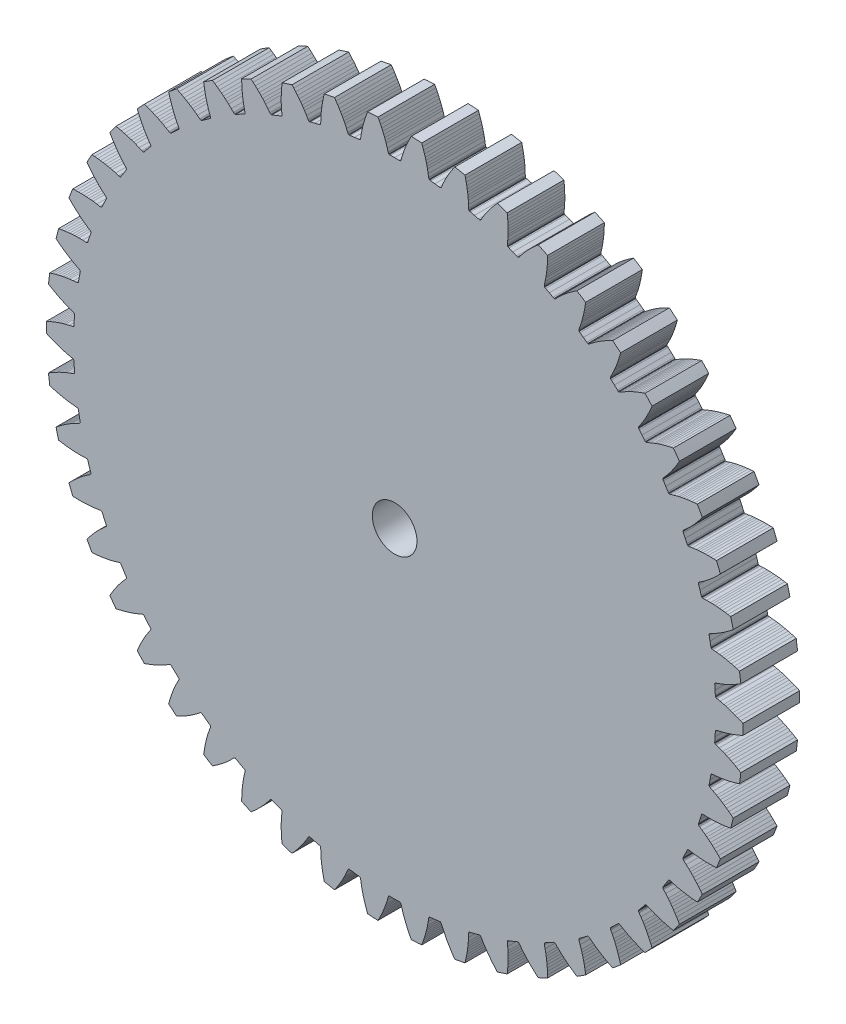
SolidWorks part; units mm, degrees
ref_plane "Front Plane" through (0, 0, 0) normal (0, 0, 1) x (1, 0, 0)
ref_plane "Top Plane" through (0, 0, 0) normal (0, 1, 0) x (1, 0, 0)
ref_plane "Right Plane" through (0, 0, 0) normal (1, 0, 0) x (0, 0, -1)
sketch "Model" plane through (0, 0, 0) normal (0, 0, 1) x (1, 0, 0)
  line L0 (38.4997, 4.1522) -> (38.2158, 3.988)
  line L1 (38.2158, 3.988) -> (37.9422, 3.8372)
  line L2 (37.9422, 3.8372) -> (37.6778, 3.6986)
  line L3 (37.6778, 3.6986) -> (37.4251, 3.5729)
  line L4 (37.4251, 3.5729) -> (37.1851, 3.4597)
  line L5 (37.1851, 3.4597) -> (36.9555, 3.3572)
  line L6 (36.9555, 3.3572) -> (36.7379, 3.2654)
  line L7 (36.7379, 3.2654) -> (36.3414, 3.1126)
  line L8 (36.3414, 3.1126) -> (36.0208, 3.0018)
  line L9 (36.0208, 3.0018) -> (35.95, 2.9701)
  line L10 (35.95, 2.9701) -> (35.8964, 2.9371)
  line L11 (35.8964, 2.9371) -> (35.8599, 2.9035)
  line L12 (35.8599, 2.9035) -> (35.8405, 2.87)
  line L13 (35.8405, 2.87) -> (35.8373, 2.8536)
  line L14 (35.8373, 2.8536) -> (35.8466, 2.7264)
  line L15 (35.8466, 2.7264) -> (35.8791, 2.2573)
  line L16 (35.8791, 2.2573) -> (35.9056, 1.7878)
  line L17 (35.9056, 1.7878) -> (35.9123, 1.6605)
  line L18 (35.9123, 1.6605) -> (35.9176, 1.6446)
  line L19 (35.9176, 1.6446) -> (35.941, 1.6138)
  line L20 (35.941, 1.6138) -> (35.9814, 1.585)
  line L21 (35.9814, 1.585) -> (36.0388, 1.559)
  line L22 (36.0388, 1.559) -> (36.113, 1.5364)
  line L23 (36.113, 1.5364) -> (36.4449, 1.4667)
  line L24 (36.4449, 1.4667) -> (36.8574, 1.3648)
  line L25 (36.8574, 1.3648) -> (37.0848, 1.3011)
  line L26 (37.0848, 1.3011) -> (37.3255, 1.2281)
  line L27 (37.3255, 1.2281) -> (37.5778, 1.1459)
  line L28 (37.5778, 1.1459) -> (37.8442, 1.0528)
  line L29 (37.8442, 1.0528) -> (38.1239, 0.9485)
  line L30 (38.1239, 0.9485) -> (38.4143, 0.8332)
  line L31 (38.4143, 0.8332) -> (38.7165, 0.7058)
  line L32 (38.7165, 0.7058) -> (38.9957, 0.5815)
  line L33 (38.9957, -0.5815) -> (38.7165, -0.7058)
  line L34 (38.7165, -0.7058) -> (38.4143, -0.8332)
  line L35 (38.4143, -0.8332) -> (38.1239, -0.9485)
  line L36 (38.1239, -0.9485) -> (37.8442, -1.0528)
  line L37 (37.8442, -1.0528) -> (37.5778, -1.1459)
  line L38 (37.5778, -1.1459) -> (37.3255, -1.2281)
  line L39 (37.3255, -1.2281) -> (37.0848, -1.3011)
  line L40 (37.0848, -1.3011) -> (36.8574, -1.3648)
  line L41 (36.8574, -1.3648) -> (36.4449, -1.4667)
  line L42 (36.4449, -1.4667) -> (36.113, -1.5364)
  line L43 (36.113, -1.5364) -> (36.0388, -1.559)
  line L44 (36.0388, -1.559) -> (35.9814, -1.585)
  line L45 (35.9814, -1.585) -> (35.941, -1.6138)
  line L46 (35.941, -1.6138) -> (35.9176, -1.6446)
  line L47 (35.9176, -1.6446) -> (35.9123, -1.6605)
  line L48 (35.9123, -1.6605) -> (35.9056, -1.7878)
  line L49 (35.9056, -1.7878) -> (35.8791, -2.2573)
  line L50 (35.8791, -2.2573) -> (35.8466, -2.7264)
  line L51 (35.8466, -2.7264) -> (35.8373, -2.8536)
  line L52 (35.8373, -2.8536) -> (35.8405, -2.87)
  line L53 (35.8405, -2.87) -> (35.8599, -2.9035)
  line L54 (35.8599, -2.9035) -> (35.8964, -2.9371)
  line L55 (35.8964, -2.9371) -> (35.95, -2.9701)
  line L56 (35.95, -2.9701) -> (36.0208, -3.0018)
  line L57 (36.0208, -3.0018) -> (36.3414, -3.1126)
  line L58 (36.3414, -3.1126) -> (36.7379, -3.2654)
  line L59 (36.7379, -3.2654) -> (36.9555, -3.3572)
  line L60 (36.9555, -3.3572) -> (37.1851, -3.4597)
  line L61 (37.1851, -3.4597) -> (37.4251, -3.5729)
  line L62 (37.4251, -3.5729) -> (37.6778, -3.6986)
  line L63 (37.6778, -3.6986) -> (37.9422, -3.8372)
  line L64 (37.9422, -3.8372) -> (38.2158, -3.988)
  line L65 (38.2158, -3.988) -> (38.4997, -4.1522)
  line L66 (38.4997, -4.1522) -> (38.7611, -4.3105)
  line L67 (38.6153, -5.4644) -> (38.3228, -5.5527)
  line L68 (38.3228, -5.5527) -> (38.007, -5.6412)
  line L69 (38.007, -5.6412) -> (37.7044, -5.7192)
  line L70 (37.7044, -5.7192) -> (37.4139, -5.7876)
  line L71 (37.4139, -5.7876) -> (37.1378, -5.8466)
  line L72 (37.1378, -5.8466) -> (36.8772, -5.8966)
  line L73 (36.8772, -5.8966) -> (36.6293, -5.9388)
  line L74 (36.6293, -5.9388) -> (36.3957, -5.9735)
  line L75 (36.3957, -5.9735) -> (35.9737, -6.0229)
  line L76 (35.9737, -6.0229) -> (35.6356, -6.0505)
  line L77 (35.6356, -6.0505) -> (35.5592, -6.0636)
  line L78 (35.5592, -6.0636) -> (35.499, -6.0822)
  line L79 (35.499, -6.0822) -> (35.4553, -6.1057)
  line L80 (35.4553, -6.1057) -> (35.4283, -6.1333)
  line L81 (35.4283, -6.1333) -> (35.421, -6.1485)
  line L82 (35.421, -6.1485) -> (35.3984, -6.2739)
  line L83 (35.3984, -6.2739) -> (35.3132, -6.7364)
  line L84 (35.3132, -6.7364) -> (35.2222, -7.1977)
  line L85 (35.2222, -7.1977) -> (35.197, -7.3227)
  line L86 (35.197, -7.3227) -> (35.1982, -7.3394)
  line L87 (35.1982, -7.3394) -> (35.2132, -7.3751)
  line L88 (35.2132, -7.3751) -> (35.2452, -7.413)
  line L89 (35.2452, -7.413) -> (35.2943, -7.4524)
  line L90 (35.2943, -7.4524) -> (35.3605, -7.4928)
  line L91 (35.3605, -7.4928) -> (35.6647, -7.6428)
  line L92 (35.6647, -7.6428) -> (36.0389, -7.8441)
  line L93 (36.0389, -7.8441) -> (36.2433, -7.9624)
  line L94 (36.2433, -7.9624) -> (36.4583, -8.0929)
  line L95 (36.4583, -8.0929) -> (36.6821, -8.2353)
  line L96 (36.6821, -8.2353) -> (36.9171, -8.3917)
  line L97 (36.9171, -8.3917) -> (37.1621, -8.5624)
  line L98 (37.1621, -8.5624) -> (37.4147, -8.7463)
  line L99 (37.4147, -8.7463) -> (37.6757, -8.9448)
  line L100 (37.6757, -8.9448) -> (37.9152, -9.1346)
  line L101 (37.6259, -10.2611) -> (37.3246, -10.3121)
  line L102 (37.3246, -10.3121) -> (37.0003, -10.3602)
  line L103 (37.0003, -10.3602) -> (36.6903, -10.3997)
  line L104 (36.6903, -10.3997) -> (36.3935, -10.4312)
  line L105 (36.3935, -10.4312) -> (36.1122, -10.4551)
  line L106 (36.1122, -10.4551) -> (35.8474, -10.472)
  line L107 (35.8474, -10.472) -> (35.5962, -10.4828)
  line L108 (35.5962, -10.4828) -> (35.3601, -10.488)
  line L109 (35.3601, -10.488) -> (34.9352, -10.4841)
  line L110 (34.9352, -10.4841) -> (34.5963, -10.4691)
  line L111 (34.5963, -10.4691) -> (34.5188, -10.4725)
  line L112 (34.5188, -10.4725) -> (34.4568, -10.4835)
  line L113 (34.4568, -10.4835) -> (34.4105, -10.5013)
  line L114 (34.4105, -10.5013) -> (34.3802, -10.5253)
  line L115 (34.3802, -10.5253) -> (34.3711, -10.5394)
  line L116 (34.3711, -10.5394) -> (34.333, -10.661)
  line L117 (34.333, -10.661) -> (34.1905, -11.1092)
  line L118 (34.1905, -11.1092) -> (34.0424, -11.5555)
  line L119 (34.0424, -11.5555) -> (34.0017, -11.6763)
  line L120 (34.0017, -11.6763) -> (34.0008, -11.6931)
  line L121 (34.0008, -11.6931) -> (34.0112, -11.7303)
  line L122 (34.0112, -11.7303) -> (34.0382, -11.7719)
  line L123 (34.0382, -11.7719) -> (34.0819, -11.8172)
  line L124 (34.0819, -11.8172) -> (34.1426, -11.8655)
  line L125 (34.1426, -11.8655) -> (34.4256, -12.0525)
  line L126 (34.4256, -12.0525) -> (34.7716, -12.2992)
  line L127 (34.7716, -12.2992) -> (34.9595, -12.4421)
  line L128 (34.9595, -12.4421) -> (35.1565, -12.5985)
  line L129 (35.1565, -12.5985) -> (35.3607, -12.7679)
  line L130 (35.3607, -12.7679) -> (35.5742, -12.9525)
  line L131 (35.5742, -12.9525) -> (35.7959, -13.1525)
  line L132 (35.7959, -13.1525) -> (36.0234, -13.3666)
  line L133 (36.0234, -13.3666) -> (36.2575, -13.5962)
  line L134 (36.2575, -13.5962) -> (36.4713, -13.8146)
  line L135 (36.0432, -14.8959) -> (35.7379, -14.9088)
  line L136 (35.7379, -14.9088) -> (35.41, -14.9159)
  line L137 (35.41, -14.9159) -> (35.0976, -14.9162)
  line L138 (35.0976, -14.9162) -> (34.7991, -14.9103)
  line L139 (34.7991, -14.9103) -> (34.5171, -14.8987)
  line L140 (34.5171, -14.8987) -> (34.2523, -14.8823)
  line L141 (34.2523, -14.8823) -> (34.0016, -14.8615)
  line L142 (34.0016, -14.8615) -> (33.7668, -14.8371)
  line L143 (33.7668, -14.8371) -> (33.3457, -14.78)
  line L144 (33.3457, -14.78) -> (33.0114, -14.7226)
  line L145 (33.0114, -14.7226) -> (32.9341, -14.7163)
  line L146 (32.9341, -14.7163) -> (32.8712, -14.7194)
  line L147 (32.8712, -14.7194) -> (32.823, -14.7312)
  line L148 (32.823, -14.7312) -> (32.7899, -14.7513)
  line L149 (32.7899, -14.7513) -> (32.7791, -14.7641)
  line L150 (32.7791, -14.7641) -> (32.7261, -14.88)
  line L151 (32.7261, -14.88) -> (32.5285, -15.3068)
  line L152 (32.5285, -15.3068) -> (32.3256, -15.731)
  line L153 (32.3256, -15.731) -> (32.2702, -15.8457)
  line L154 (32.2702, -15.8457) -> (32.2671, -15.8623)
  line L155 (32.2671, -15.8623) -> (32.2728, -15.9005)
  line L156 (32.2728, -15.9005) -> (32.2944, -15.9452)
  line L157 (32.2944, -15.9452) -> (32.3321, -15.9956)
  line L158 (32.3321, -15.9956) -> (32.3862, -16.0512)
  line L159 (32.3862, -16.0512) -> (32.6436, -16.2722)
  line L160 (32.6436, -16.2722) -> (32.9559, -16.5602)
  line L161 (32.9559, -16.5602) -> (33.1245, -16.7256)
  line L162 (33.1245, -16.7256) -> (33.3002, -16.9055)
  line L163 (33.3002, -16.9055) -> (33.4817, -17.0991)
  line L164 (33.4817, -17.0991) -> (33.6703, -17.309)
  line L165 (33.6703, -17.309) -> (33.8652, -17.5352)
  line L166 (33.8652, -17.5352) -> (34.0641, -17.7761)
  line L167 (34.0641, -17.7761) -> (34.2676, -18.0333)
  line L168 (34.2676, -18.0333) -> (34.4523, -18.2767)
  line L169 (33.892, -19.2959) -> (33.5875, -19.2703)
  line L170 (33.5875, -19.2703) -> (33.2613, -19.2364)
  line L171 (33.2613, -19.2364) -> (32.9513, -19.1975)
  line L172 (32.9513, -19.1975) -> (32.656, -19.1542)
  line L173 (32.656, -19.1542) -> (32.3776, -19.1074)
  line L174 (32.3776, -19.1074) -> (32.1169, -19.0579)
  line L175 (32.1169, -19.0579) -> (31.8709, -19.0059)
  line L176 (31.8709, -19.0059) -> (31.6409, -18.9522)
  line L177 (31.6409, -18.9522) -> (31.2303, -18.8428)
  line L178 (31.2303, -18.8428) -> (30.9058, -18.7439)
  line L179 (30.9058, -18.7439) -> (30.83, -18.728)
  line L180 (30.83, -18.728) -> (30.7672, -18.7232)
  line L181 (30.7672, -18.7232) -> (30.7179, -18.7289)
  line L182 (30.7179, -18.7289) -> (30.6826, -18.7446)
  line L183 (30.6826, -18.7446) -> (30.6702, -18.756)
  line L184 (30.6702, -18.756) -> (30.6031, -18.8644)
  line L185 (30.6031, -18.8644) -> (30.3536, -19.263)
  line L186 (30.3536, -19.263) -> (30.0991, -19.6584)
  line L187 (30.0991, -19.6584) -> (30.0297, -19.7653)
  line L188 (30.0297, -19.7653) -> (30.0246, -19.7813)
  line L189 (30.0246, -19.7813) -> (30.0254, -19.82)
  line L190 (30.0254, -19.82) -> (30.0412, -19.867)
  line L191 (30.0412, -19.867) -> (30.0724, -19.9218)
  line L192 (30.0724, -19.9218) -> (30.1191, -19.9837)
  line L193 (30.1191, -19.9837) -> (30.3467, -20.2352)
  line L194 (30.3467, -20.2352) -> (30.6205, -20.5601)
  line L195 (30.6205, -20.5601) -> (30.767, -20.7453)
  line L196 (30.767, -20.7453) -> (30.9188, -20.9458)
  line L197 (30.9188, -20.9458) -> (31.0746, -21.1606)
  line L198 (31.0746, -21.1606) -> (31.2354, -21.3925)
  line L199 (31.2354, -21.3925) -> (31.4004, -21.6414)
  line L200 (31.4004, -21.6414) -> (31.5676, -21.9053)
  line L201 (31.5676, -21.9053) -> (31.7372, -22.186)
  line L202 (31.7372, -22.186) -> (31.89, -22.4506)
  line L203 (31.2064, -23.3915) -> (30.9074, -23.328)
  line L204 (30.9074, -23.328) -> (30.5881, -23.2534)
  line L205 (30.5881, -23.2534) -> (30.2854, -23.176)
  line L206 (30.2854, -23.176) -> (29.9978, -23.096)
  line L207 (29.9978, -23.096) -> (29.7275, -23.0147)
  line L208 (29.7275, -23.0147) -> (29.4751, -22.9329)
  line L209 (29.4751, -22.9329) -> (29.2375, -22.8505)
  line L210 (29.2375, -22.8505) -> (29.0161, -22.7684)
  line L211 (29.0161, -22.7684) -> (28.6225, -22.6084)
  line L212 (28.6225, -22.6084) -> (28.3129, -22.4697)
  line L213 (28.3129, -22.4697) -> (28.2396, -22.4443)
  line L214 (28.2396, -22.4443) -> (28.1779, -22.4317)
  line L215 (28.1779, -22.4317) -> (28.1283, -22.4312)
  line L216 (28.1283, -22.4312) -> (28.0913, -22.4423)
  line L217 (28.0913, -22.4423) -> (28.0776, -22.4521)
  line L218 (28.0776, -22.4521) -> (27.9974, -22.5512)
  line L219 (27.9974, -22.5512) -> (27.7, -22.9154)
  line L220 (27.7, -22.9154) -> (27.3979, -23.2758)
  line L221 (27.3979, -23.2758) -> (27.3157, -23.3732)
  line L222 (27.3157, -23.3732) -> (27.3086, -23.3884)
  line L223 (27.3086, -23.3884) -> (27.3046, -23.4269)
  line L224 (27.3046, -23.4269) -> (27.3144, -23.4755)
  line L225 (27.3144, -23.4755) -> (27.3384, -23.5338)
  line L226 (27.3384, -23.5338) -> (27.377, -23.601)
  line L227 (27.377, -23.601) -> (27.5713, -23.8791)
  line L228 (27.5713, -23.8791) -> (27.8022, -24.2358)
  line L229 (27.8022, -24.2358) -> (27.9243, -24.4379)
  line L230 (27.9243, -24.4379) -> (28.0498, -24.6558)
  line L231 (28.0498, -24.6558) -> (28.1774, -24.8884)
  line L232 (28.1774, -24.8884) -> (28.308, -25.1387)
  line L233 (28.308, -25.1387) -> (28.4404, -25.4062)
  line L234 (28.4404, -25.4062) -> (28.5732, -25.6891)
  line L235 (28.5732, -25.6891) -> (28.7063, -25.9888)
  line L236 (28.7063, -25.9888) -> (28.8247, -26.2705)
  line L237 (28.0285, -27.1183) -> (27.74, -27.0178)
  line L238 (27.74, -27.0178) -> (27.4325, -26.9038)
  line L239 (27.4325, -26.9038) -> (27.1419, -26.789)
  line L240 (27.1419, -26.789) -> (26.8666, -26.6736)
  line L241 (26.8666, -26.6736) -> (26.6086, -26.5591)
  line L242 (26.6086, -26.5591) -> (26.3684, -26.4463)
  line L243 (26.3684, -26.4463) -> (26.143, -26.3347)
  line L244 (26.143, -26.3347) -> (25.9336, -26.2255)
  line L245 (25.9336, -26.2255) -> (25.5632, -26.0175)
  line L246 (25.5632, -26.0175) -> (25.2735, -25.841)
  line L247 (25.2735, -25.841) -> (25.2039, -25.8067)
  line L248 (25.2039, -25.8067) -> (25.1443, -25.7864)
  line L249 (25.1443, -25.7864) -> (25.0952, -25.7797)
  line L250 (25.0952, -25.7797) -> (25.057, -25.7862)
  line L251 (25.057, -25.7862) -> (25.0422, -25.7941)
  line L252 (25.0422, -25.7941) -> (24.9502, -25.8824)
  line L253 (24.9502, -25.8824) -> (24.6095, -26.2064)
  line L254 (24.6095, -26.2064) -> (24.2647, -26.5262)
  line L255 (24.2647, -26.5262) -> (24.1708, -26.6124)
  line L256 (24.1708, -26.6124) -> (24.1619, -26.6267)
  line L257 (24.1619, -26.6267) -> (24.1531, -26.6644)
  line L258 (24.1531, -26.6644) -> (24.1567, -26.7138)
  line L259 (24.1567, -26.7138) -> (24.1732, -26.7746)
  line L260 (24.1732, -26.7746) -> (24.2031, -26.8462)
  line L261 (24.2031, -26.8462) -> (24.361, -27.1464)
  line L262 (24.361, -27.1464) -> (24.5454, -27.5292)
  line L263 (24.5454, -27.5292) -> (24.6412, -27.745)
  line L264 (24.6412, -27.745) -> (24.7385, -27.9769)
  line L265 (24.7385, -27.9769) -> (24.8359, -28.2237)
  line L266 (24.8359, -28.2237) -> (24.934, -28.4884)
  line L267 (24.934, -28.4884) -> (25.0319, -28.7704)
  line L268 (25.0319, -28.7704) -> (25.1282, -29.0677)
  line L269 (25.1282, -29.0677) -> (25.2227, -29.3817)
  line L270 (25.2227, -29.3817) -> (25.3048, -29.676)
  line L271 (24.4087, -30.4173) -> (24.135, -30.2815)
  line L272 (24.135, -30.2815) -> (23.8442, -30.1298)
  line L273 (23.8442, -30.1298) -> (23.5703, -29.9796)
  line L274 (23.5703, -29.9796) -> (23.3116, -29.8306)
  line L275 (23.3116, -29.8306) -> (23.07, -29.6846)
  line L276 (23.07, -29.6846) -> (22.8459, -29.5426)
  line L277 (22.8459, -29.5426) -> (22.6363, -29.4037)
  line L278 (22.6363, -29.4037) -> (22.4422, -29.2691)
  line L279 (22.4422, -29.2691) -> (22.1007, -29.0162)
  line L280 (22.1007, -29.0162) -> (21.8354, -28.8049)
  line L281 (21.8354, -28.8049) -> (21.7707, -28.7621)
  line L282 (21.7707, -28.7621) -> (21.7141, -28.7345)
  line L283 (21.7141, -28.7345) -> (21.6662, -28.7217)
  line L284 (21.6662, -28.7217) -> (21.6276, -28.7233)
  line L285 (21.6276, -28.7233) -> (21.6119, -28.7294)
  line L286 (21.6119, -28.7294) -> (21.5096, -28.8054)
  line L287 (21.5096, -28.8054) -> (21.1309, -29.0842)
  line L288 (21.1309, -29.0842) -> (20.7487, -29.3582)
  line L289 (20.7487, -29.3582) -> (20.6448, -29.432)
  line L290 (20.6448, -29.432) -> (20.6342, -29.445)
  line L291 (20.6342, -29.445) -> (20.6207, -29.4813)
  line L292 (20.6207, -29.4813) -> (20.6181, -29.5308)
  line L293 (20.6181, -29.5308) -> (20.6269, -29.5932)
  line L294 (20.6269, -29.5932) -> (20.6475, -29.6679)
  line L295 (20.6475, -29.6679) -> (20.7666, -29.9856)
  line L296 (20.7666, -29.9856) -> (20.9015, -30.3885)
  line L297 (20.9015, -30.3885) -> (20.9696, -30.6146)
  line L298 (20.9696, -30.6146) -> (21.0369, -30.8569)
  line L299 (21.0369, -30.8569) -> (21.1027, -31.1139)
  line L300 (21.1027, -31.1139) -> (21.1669, -31.3888)
  line L301 (21.1669, -31.3888) -> (21.2287, -31.6809)
  line L302 (21.2287, -31.6809) -> (21.2869, -31.9879)
  line L303 (21.2869, -31.9879) -> (21.3413, -32.3112)
  line L304 (21.3413, -32.3112) -> (21.3859, -32.6135)
  line L305 (20.4039, -33.2367) -> (20.1494, -33.0676)
  line L306 (20.1494, -33.0676) -> (19.88, -32.8807)
  line L307 (19.88, -32.8807) -> (19.627, -32.6973)
  line L308 (19.627, -32.6973) -> (19.389, -32.5171)
  line L309 (19.389, -32.5171) -> (19.1677, -32.3419)
  line L310 (19.1677, -32.3419) -> (18.9631, -32.173)
  line L311 (18.9631, -32.173) -> (18.7725, -32.0089)
  line L312 (18.7725, -32.0089) -> (18.5969, -31.8511)
  line L313 (18.5969, -31.8511) -> (18.2898, -31.5574)
  line L314 (18.2898, -31.5574) -> (18.053, -31.3144)
  line L315 (18.053, -31.3144) -> (17.9942, -31.2639)
  line L316 (17.9942, -31.2639) -> (17.9415, -31.2294)
  line L317 (17.9415, -31.2294) -> (17.8956, -31.2107)
  line L318 (17.8956, -31.2107) -> (17.857, -31.2075)
  line L319 (17.857, -31.2075) -> (17.8407, -31.2115)
  line L320 (17.8407, -31.2115) -> (17.7297, -31.2741)
  line L321 (17.7297, -31.2741) -> (17.319, -31.5032)
  line L322 (17.319, -31.5032) -> (16.9055, -31.7272)
  line L323 (16.9055, -31.7272) -> (16.7932, -31.7874)
  line L324 (16.7932, -31.7874) -> (16.781, -31.799)
  line L325 (16.781, -31.799) -> (16.7631, -31.8333)
  line L326 (16.7631, -31.8333) -> (16.7543, -31.8821)
  line L327 (16.7543, -31.8821) -> (16.7552, -31.9451)
  line L328 (16.7552, -31.9451) -> (16.7664, -32.0218)
  line L329 (16.7664, -32.0218) -> (16.8446, -32.3519)
  line L330 (16.8446, -32.3519) -> (16.928, -32.7685)
  line L331 (16.928, -32.7685) -> (16.9672, -33.0014)
  line L332 (16.9672, -33.0014) -> (17.0037, -33.2502)
  line L333 (17.0037, -33.2502) -> (17.0367, -33.5135)
  line L334 (17.0367, -33.5135) -> (17.0659, -33.7942)
  line L335 (17.0659, -33.7942) -> (17.0906, -34.0917)
  line L336 (17.0906, -34.0917) -> (17.1099, -34.4036)
  line L337 (17.1099, -34.4036) -> (17.1233, -34.7312)
  line L338 (17.1233, -34.7312) -> (17.1297, -35.0367)
  line L339 (16.0774, -35.5319) -> (15.846, -35.3323)
  line L340 (15.846, -35.3323) -> (15.6022, -35.1131)
  line L341 (15.6022, -35.1131) -> (15.3742, -34.8994)
  line L342 (15.3742, -34.8994) -> (15.1607, -34.6907)
  line L343 (15.1607, -34.6907) -> (14.963, -34.4893)
  line L344 (14.963, -34.4893) -> (14.7812, -34.296)
  line L345 (14.7812, -34.296) -> (14.6127, -34.1093)
  line L346 (14.6127, -34.1093) -> (14.4582, -33.9307)
  line L347 (14.4582, -33.9307) -> (14.1904, -33.6009)
  line L348 (14.1904, -33.6009) -> (13.9859, -33.3302)
  line L349 (13.9859, -33.3302) -> (13.9339, -33.2727)
  line L350 (13.9339, -33.2727) -> (13.886, -33.2318)
  line L351 (13.886, -33.2318) -> (13.8427, -33.2075)
  line L352 (13.8427, -33.2075) -> (13.8049, -33.1995)
  line L353 (13.8049, -33.1995) -> (13.7882, -33.2015)
  line L354 (13.7882, -33.2015) -> (13.6702, -33.2496)
  line L355 (13.6702, -33.2496) -> (13.2341, -33.4255)
  line L356 (13.2341, -33.4255) -> (12.7958, -33.5958)
  line L357 (12.7958, -33.5958) -> (12.6768, -33.6415)
  line L358 (12.6768, -33.6415) -> (12.6633, -33.6515)
  line L359 (12.6633, -33.6515) -> (12.6412, -33.6832)
  line L360 (12.6412, -33.6832) -> (12.6263, -33.7306)
  line L361 (12.6263, -33.7306) -> (12.6193, -33.7932)
  line L362 (12.6193, -33.7932) -> (12.6208, -33.8707)
  line L363 (12.6208, -33.8707) -> (12.6571, -34.208)
  line L364 (12.6571, -34.208) -> (12.6876, -34.6318)
  line L365 (12.6876, -34.6318) -> (12.6972, -34.8677)
  line L366 (12.6972, -34.8677) -> (12.7022, -35.1191)
  line L367 (12.7022, -35.1191) -> (12.702, -35.3845)
  line L368 (12.702, -35.3845) -> (12.6958, -35.6667)
  line L369 (12.6958, -35.6667) -> (12.683, -35.9649)
  line L370 (12.683, -35.9649) -> (12.6631, -36.2767)
  line L371 (12.6631, -36.2767) -> (12.6353, -36.6035)
  line L372 (12.6353, -36.6035) -> (12.6034, -36.9074)
  line L373 (11.4973, -37.2668) -> (11.2928, -37.0397)
  line L374 (11.2928, -37.0397) -> (11.0783, -36.7917)
  line L375 (11.0783, -36.7917) -> (10.8789, -36.5511)
  line L376 (10.8789, -36.5511) -> (10.6932, -36.3173)
  line L377 (10.6932, -36.3173) -> (10.5224, -36.0927)
  line L378 (10.5224, -36.0927) -> (10.3662, -35.8782)
  line L379 (10.3662, -35.8782) -> (10.2225, -35.6718)
  line L380 (10.2225, -35.6718) -> (10.0916, -35.4752)
  line L381 (10.0916, -35.4752) -> (9.8672, -35.1145)
  line L382 (9.8672, -35.1145) -> (9.6983, -34.8202)
  line L383 (9.6983, -34.8202) -> (9.6539, -34.7567)
  line L384 (9.6539, -34.7567) -> (9.6114, -34.7102)
  line L385 (9.6114, -34.7102) -> (9.5716, -34.6806)
  line L386 (9.5716, -34.6806) -> (9.5351, -34.6679)
  line L387 (9.5351, -34.6679) -> (9.5182, -34.6678)
  line L388 (9.5182, -34.6678) -> (9.3951, -34.7008)
  line L389 (9.3951, -34.7008) -> (8.9404, -34.8206)
  line L390 (8.9404, -34.8206) -> (8.4842, -34.9346)
  line L391 (8.4842, -34.9346) -> (8.3604, -34.965)
  line L392 (8.3604, -34.965) -> (8.3457, -34.9732)
  line L393 (8.3457, -34.9732) -> (8.3199, -35.002)
  line L394 (8.3199, -35.002) -> (8.2992, -35.0471)
  line L395 (8.2992, -35.0471) -> (8.2844, -35.1083)
  line L396 (8.2844, -35.1083) -> (8.2761, -35.1854)
  line L397 (8.2761, -35.1854) -> (8.2699, -35.5246)
  line L398 (8.2699, -35.5246) -> (8.247, -35.9488)
  line L399 (8.247, -35.9488) -> (8.227, -36.1841)
  line L400 (8.227, -36.1841) -> (8.2005, -36.4342)
  line L401 (8.2005, -36.4342) -> (8.167, -36.6974)
  line L402 (8.167, -36.6974) -> (8.1255, -36.9766)
  line L403 (8.1255, -36.9766) -> (8.0754, -37.2709)
  line L404 (8.0754, -37.2709) -> (8.0165, -37.5778)
  line L405 (8.0165, -37.5778) -> (7.9481, -37.8985)
  line L406 (7.9481, -37.8985) -> (7.8783, -38.196)
  line L407 (6.7359, -38.4139) -> (6.5614, -38.163)
  line L408 (6.5614, -38.163) -> (6.3797, -37.89)
  line L409 (6.3797, -37.89) -> (6.212, -37.6264)
  line L410 (6.212, -37.6264) -> (6.0571, -37.3712)
  line L411 (6.0571, -37.3712) -> (5.9158, -37.1269)
  line L412 (5.9158, -37.1269) -> (5.7877, -36.8945)
  line L413 (5.7877, -36.8945) -> (5.671, -36.6717)
  line L414 (5.671, -36.6717) -> (5.5658, -36.4603)
  line L415 (5.5658, -36.4603) -> (5.3884, -36.0742)
  line L416 (5.3884, -36.0742) -> (5.2577, -35.7612)
  line L417 (5.2577, -35.7612) -> (5.2216, -35.6926)
  line L418 (5.2216, -35.6926) -> (5.1853, -35.6411)
  line L419 (5.1853, -35.6411) -> (5.1495, -35.6068)
  line L420 (5.1495, -35.6068) -> (5.1148, -35.5896)
  line L421 (5.1148, -35.5896) -> (5.0982, -35.5874)
  line L422 (5.0982, -35.5874) -> (4.9719, -35.6047)
  line L423 (4.9719, -35.6047) -> (4.5057, -35.6665)
  line L424 (4.5057, -35.6665) -> (4.0388, -35.7225)
  line L425 (4.0388, -35.7225) -> (3.9122, -35.7372)
  line L426 (3.9122, -35.7372) -> (3.8966, -35.7435)
  line L427 (3.8966, -35.7435) -> (3.8674, -35.7688)
  line L428 (3.8674, -35.7688) -> (3.8412, -35.8109)
  line L429 (3.8412, -35.8109) -> (3.8188, -35.8698)
  line L430 (3.8188, -35.8698) -> (3.801, -35.9452)
  line L431 (3.801, -35.9452) -> (3.7522, -36.2809)
  line L432 (3.7522, -36.2809) -> (3.6764, -36.699)
  line L433 (3.6764, -36.699) -> (3.6271, -36.9299)
  line L434 (3.6271, -36.9299) -> (3.5694, -37.1747)
  line L435 (3.5694, -37.1747) -> (3.5032, -37.4316)
  line L436 (3.5032, -37.4316) -> (3.427, -37.7034)
  line L437 (3.427, -37.7034) -> (3.3404, -37.9892)
  line L438 (3.3404, -37.9892) -> (3.2436, -38.2862)
  line L439 (3.2436, -38.2862) -> (3.1355, -38.5958)
  line L440 (3.1355, -38.5958) -> (3.0289, -38.8822)
  line L441 (1.8682, -38.9552) -> (1.7266, -38.6844)
  line L442 (1.7266, -38.6844) -> (1.5805, -38.3908)
  line L443 (1.5805, -38.3908) -> (1.4472, -38.1083)
  line L444 (1.4472, -38.1083) -> (1.3255, -37.8357)
  line L445 (1.3255, -37.8357) -> (1.2159, -37.5755)
  line L446 (1.2159, -37.5755) -> (1.118, -37.3289)
  line L447 (1.118, -37.3289) -> (1.0301, -37.0933)
  line L448 (1.0301, -37.0933) -> (0.9522, -36.8704)
  line L449 (0.9522, -36.8704) -> (0.8246, -36.4651)
  line L450 (0.8246, -36.4651) -> (0.7342, -36.1382)
  line L451 (0.7342, -36.1382) -> (0.707, -36.0656)
  line L452 (0.707, -36.0656) -> (0.6774, -36.01)
  line L453 (0.6774, -36.01) -> (0.6462, -35.9714)
  line L454 (0.6462, -35.9714) -> (0.6139, -35.95)
  line L455 (0.6139, -35.95) -> (0.5977, -35.9457)
  line L456 (0.5977, -35.9457) -> (0.4702, -35.947)
  line L457 (0.4702, -35.947) -> (0, -35.95)
  line L458 (0, -35.95) -> (-0.4702, -35.947)
  line L459 (-0.4702, -35.947) -> (-0.5977, -35.9457)
  line L460 (-0.5977, -35.9457) -> (-0.6139, -35.95)
  line L461 (-0.6139, -35.95) -> (-0.6462, -35.9714)
  line L462 (-0.6462, -35.9714) -> (-0.6774, -36.01)
  line L463 (-0.6774, -36.01) -> (-0.707, -36.0656)
  line L464 (-0.707, -36.0656) -> (-0.7342, -36.1382)
  line L465 (-0.7342, -36.1382) -> (-0.8246, -36.4651)
  line L466 (-0.8246, -36.4651) -> (-0.9522, -36.8704)
  line L467 (-0.9522, -36.8704) -> (-1.0301, -37.0933)
  line L468 (-1.0301, -37.0933) -> (-1.118, -37.3289)
  line L469 (-1.118, -37.3289) -> (-1.2159, -37.5755)
  line L470 (-1.2159, -37.5755) -> (-1.3255, -37.8357)
  line L471 (-1.3255, -37.8357) -> (-1.4472, -38.1083)
  line L472 (-1.4472, -38.1083) -> (-1.5805, -38.3908)
  line L473 (-1.5805, -38.3908) -> (-1.7266, -38.6844)
  line L474 (-1.7266, -38.6844) -> (-1.8682, -38.9552)
  line L475 (-3.0289, -38.8822) -> (-3.1355, -38.5958)
  line L476 (-3.1355, -38.5958) -> (-3.2436, -38.2862)
  line L477 (-3.2436, -38.2862) -> (-3.3404, -37.9892)
  line L478 (-3.3404, -37.9892) -> (-3.427, -37.7034)
  line L479 (-3.427, -37.7034) -> (-3.5032, -37.4316)
  line L480 (-3.5032, -37.4316) -> (-3.5694, -37.1747)
  line L481 (-3.5694, -37.1747) -> (-3.6271, -36.9299)
  line L482 (-3.6271, -36.9299) -> (-3.6764, -36.699)
  line L483 (-3.6764, -36.699) -> (-3.7522, -36.2809)
  line L484 (-3.7522, -36.2809) -> (-3.801, -35.9452)
  line L485 (-3.801, -35.9452) -> (-3.8188, -35.8698)
  line L486 (-3.8188, -35.8698) -> (-3.8412, -35.8109)
  line L487 (-3.8412, -35.8109) -> (-3.8674, -35.7688)
  line L488 (-3.8674, -35.7688) -> (-3.8966, -35.7435)
  line L489 (-3.8966, -35.7435) -> (-3.9122, -35.7372)
  line L490 (-3.9122, -35.7372) -> (-4.0388, -35.7225)
  line L491 (-4.0388, -35.7225) -> (-4.5057, -35.6665)
  line L492 (-4.5057, -35.6665) -> (-4.9719, -35.6047)
  line L493 (-4.9719, -35.6047) -> (-5.0982, -35.5874)
  line L494 (-5.0982, -35.5874) -> (-5.1148, -35.5896)
  line L495 (-5.1148, -35.5896) -> (-5.1495, -35.6068)
  line L496 (-5.1495, -35.6068) -> (-5.1853, -35.6411)
  line L497 (-5.1853, -35.6411) -> (-5.2216, -35.6926)
  line L498 (-5.2216, -35.6926) -> (-5.2577, -35.7612)
  line L499 (-5.2577, -35.7612) -> (-5.3884, -36.0742)
  line L500 (-5.3884, -36.0742) -> (-5.5658, -36.4603)
  line L501 (-5.5658, -36.4603) -> (-5.671, -36.6717)
  line L502 (-5.671, -36.6717) -> (-5.7877, -36.8945)
  line L503 (-5.7877, -36.8945) -> (-5.9158, -37.1269)
  line L504 (-5.9158, -37.1269) -> (-6.0571, -37.3712)
  line L505 (-6.0571, -37.3712) -> (-6.212, -37.6264)
  line L506 (-6.212, -37.6264) -> (-6.3797, -37.89)
  line L507 (-6.3797, -37.89) -> (-6.5614, -38.163)
  line L508 (-6.5614, -38.163) -> (-6.7359, -38.4139)
  line L509 (-7.8783, -38.196) -> (-7.9481, -37.8985)
  line L510 (-7.9481, -37.8985) -> (-8.0165, -37.5778)
  line L511 (-8.0165, -37.5778) -> (-8.0754, -37.2709)
  line L512 (-8.0754, -37.2709) -> (-8.1255, -36.9766)
  line L513 (-8.1255, -36.9766) -> (-8.167, -36.6974)
  line L514 (-8.167, -36.6974) -> (-8.2005, -36.4342)
  line L515 (-8.2005, -36.4342) -> (-8.227, -36.1841)
  line L516 (-8.227, -36.1841) -> (-8.247, -35.9488)
  line L517 (-8.247, -35.9488) -> (-8.2699, -35.5246)
  line L518 (-8.2699, -35.5246) -> (-8.2761, -35.1854)
  line L519 (-8.2761, -35.1854) -> (-8.2844, -35.1083)
  line L520 (-8.2844, -35.1083) -> (-8.2992, -35.0471)
  line L521 (-8.2992, -35.0471) -> (-8.3199, -35.002)
  line L522 (-8.3199, -35.002) -> (-8.3457, -34.9732)
  line L523 (-8.3457, -34.9732) -> (-8.3604, -34.965)
  line L524 (-8.3604, -34.965) -> (-8.4842, -34.9346)
  line L525 (-8.4842, -34.9346) -> (-8.9404, -34.8206)
  line L526 (-8.9404, -34.8206) -> (-9.3951, -34.7008)
  line L527 (-9.3951, -34.7008) -> (-9.5182, -34.6678)
  line L528 (-9.5182, -34.6678) -> (-9.5351, -34.6679)
  line L529 (-9.5351, -34.6679) -> (-9.5716, -34.6806)
  line L530 (-9.5716, -34.6806) -> (-9.6114, -34.7102)
  line L531 (-9.6114, -34.7102) -> (-9.6539, -34.7567)
  line L532 (-9.6539, -34.7567) -> (-9.6983, -34.8202)
  line L533 (-9.6983, -34.8202) -> (-9.8672, -35.1145)
  line L534 (-9.8672, -35.1145) -> (-10.0916, -35.4752)
  line L535 (-10.0916, -35.4752) -> (-10.2225, -35.6718)
  line L536 (-10.2225, -35.6718) -> (-10.3662, -35.8782)
  line L537 (-10.3662, -35.8782) -> (-10.5224, -36.0927)
  line L538 (-10.5224, -36.0927) -> (-10.6932, -36.3173)
  line L539 (-10.6932, -36.3173) -> (-10.8789, -36.5511)
  line L540 (-10.8789, -36.5511) -> (-11.0783, -36.7917)
  line L541 (-11.0783, -36.7917) -> (-11.2928, -37.0397)
  line L542 (-11.2928, -37.0397) -> (-11.4973, -37.2668)
  line L543 (-12.6034, -36.9074) -> (-12.6353, -36.6035)
  line L544 (-12.6353, -36.6035) -> (-12.6631, -36.2767)
  line L545 (-12.6631, -36.2767) -> (-12.683, -35.9649)
  line L546 (-12.683, -35.9649) -> (-12.6958, -35.6667)
  line L547 (-12.6958, -35.6667) -> (-12.702, -35.3845)
  line L548 (-12.702, -35.3845) -> (-12.7022, -35.1191)
  line L549 (-12.7022, -35.1191) -> (-12.6972, -34.8677)
  line L550 (-12.6972, -34.8677) -> (-12.6876, -34.6318)
  line L551 (-12.6876, -34.6318) -> (-12.6571, -34.208)
  line L552 (-12.6571, -34.208) -> (-12.6208, -33.8707)
  line L553 (-12.6208, -33.8707) -> (-12.6193, -33.7932)
  line L554 (-12.6193, -33.7932) -> (-12.6263, -33.7306)
  line L555 (-12.6263, -33.7306) -> (-12.6412, -33.6832)
  line L556 (-12.6412, -33.6832) -> (-12.6633, -33.6515)
  line L557 (-12.6633, -33.6515) -> (-12.6768, -33.6415)
  line L558 (-12.6768, -33.6415) -> (-12.7958, -33.5958)
  line L559 (-12.7958, -33.5958) -> (-13.2341, -33.4255)
  line L560 (-13.2341, -33.4255) -> (-13.6702, -33.2496)
  line L561 (-13.6702, -33.2496) -> (-13.7882, -33.2015)
  line L562 (-13.7882, -33.2015) -> (-13.8049, -33.1995)
  line L563 (-13.8049, -33.1995) -> (-13.8427, -33.2075)
  line L564 (-13.8427, -33.2075) -> (-13.886, -33.2318)
  line L565 (-13.886, -33.2318) -> (-13.9339, -33.2727)
  line L566 (-13.9339, -33.2727) -> (-13.9859, -33.3302)
  line L567 (-13.9859, -33.3302) -> (-14.1904, -33.6009)
  line L568 (-14.1904, -33.6009) -> (-14.4582, -33.9307)
  line L569 (-14.4582, -33.9307) -> (-14.6127, -34.1093)
  line L570 (-14.6127, -34.1093) -> (-14.7812, -34.296)
  line L571 (-14.7812, -34.296) -> (-14.963, -34.4893)
  line L572 (-14.963, -34.4893) -> (-15.1607, -34.6907)
  line L573 (-15.1607, -34.6907) -> (-15.3742, -34.8994)
  line L574 (-15.3742, -34.8994) -> (-15.6022, -35.1131)
  line L575 (-15.6022, -35.1131) -> (-15.846, -35.3323)
  line L576 (-15.846, -35.3323) -> (-16.0774, -35.5319)
  line L577 (-17.1297, -35.0367) -> (-17.1233, -34.7312)
  line L578 (-17.1233, -34.7312) -> (-17.1099, -34.4036)
  line L579 (-17.1099, -34.4036) -> (-17.0906, -34.0917)
  line L580 (-17.0906, -34.0917) -> (-17.0659, -33.7942)
  line L581 (-17.0659, -33.7942) -> (-17.0367, -33.5135)
  line L582 (-17.0367, -33.5135) -> (-17.0037, -33.2502)
  line L583 (-17.0037, -33.2502) -> (-16.9672, -33.0014)
  line L584 (-16.9672, -33.0014) -> (-16.928, -32.7685)
  line L585 (-16.928, -32.7685) -> (-16.8446, -32.3519)
  line L586 (-16.8446, -32.3519) -> (-16.7664, -32.0218)
  line L587 (-16.7664, -32.0218) -> (-16.7552, -31.9451)
  line L588 (-16.7552, -31.9451) -> (-16.7543, -31.8821)
  line L589 (-16.7543, -31.8821) -> (-16.7631, -31.8333)
  line L590 (-16.7631, -31.8333) -> (-16.781, -31.799)
  line L591 (-16.781, -31.799) -> (-16.7932, -31.7874)
  line L592 (-16.7932, -31.7874) -> (-16.9055, -31.7272)
  line L593 (-16.9055, -31.7272) -> (-17.319, -31.5032)
  line L594 (-17.319, -31.5032) -> (-17.7297, -31.2741)
  line L595 (-17.7297, -31.2741) -> (-17.8407, -31.2115)
  line L596 (-17.8407, -31.2115) -> (-17.857, -31.2075)
  line L597 (-17.857, -31.2075) -> (-17.8956, -31.2107)
  line L598 (-17.8956, -31.2107) -> (-17.9415, -31.2294)
  line L599 (-17.9415, -31.2294) -> (-17.9942, -31.2639)
  line L600 (-17.9942, -31.2639) -> (-18.053, -31.3144)
  line L601 (-18.053, -31.3144) -> (-18.2898, -31.5574)
  line L602 (-18.2898, -31.5574) -> (-18.5969, -31.8511)
  line L603 (-18.5969, -31.8511) -> (-18.7725, -32.0089)
  line L604 (-18.7725, -32.0089) -> (-18.9631, -32.173)
  line L605 (-18.9631, -32.173) -> (-19.1677, -32.3419)
  line L606 (-19.1677, -32.3419) -> (-19.389, -32.5171)
  line L607 (-19.389, -32.5171) -> (-19.627, -32.6973)
  line L608 (-19.627, -32.6973) -> (-19.88, -32.8807)
  line L609 (-19.88, -32.8807) -> (-20.1494, -33.0676)
  line L610 (-20.1494, -33.0676) -> (-20.4039, -33.2367)
  line L611 (-21.3859, -32.6135) -> (-21.3413, -32.3112)
  line L612 (-21.3413, -32.3112) -> (-21.2869, -31.9879)
  line L613 (-21.2869, -31.9879) -> (-21.2287, -31.6809)
  line L614 (-21.2287, -31.6809) -> (-21.1669, -31.3888)
  line L615 (-21.1669, -31.3888) -> (-21.1027, -31.1139)
  line L616 (-21.1027, -31.1139) -> (-21.0369, -30.8569)
  line L617 (-21.0369, -30.8569) -> (-20.9696, -30.6146)
  line L618 (-20.9696, -30.6146) -> (-20.9015, -30.3885)
  line L619 (-20.9015, -30.3885) -> (-20.7666, -29.9856)
  line L620 (-20.7666, -29.9856) -> (-20.6475, -29.6679)
  line L621 (-20.6475, -29.6679) -> (-20.6269, -29.5932)
  line L622 (-20.6269, -29.5932) -> (-20.6181, -29.5308)
  line L623 (-20.6181, -29.5308) -> (-20.6207, -29.4813)
  line L624 (-20.6207, -29.4813) -> (-20.6342, -29.445)
  line L625 (-20.6342, -29.445) -> (-20.6448, -29.432)
  line L626 (-20.6448, -29.432) -> (-20.7487, -29.3582)
  line L627 (-20.7487, -29.3582) -> (-21.1309, -29.0842)
  line L628 (-21.1309, -29.0842) -> (-21.5096, -28.8054)
  line L629 (-21.5096, -28.8054) -> (-21.6119, -28.7294)
  line L630 (-21.6119, -28.7294) -> (-21.6276, -28.7233)
  line L631 (-21.6276, -28.7233) -> (-21.6662, -28.7217)
  line L632 (-21.6662, -28.7217) -> (-21.7141, -28.7345)
  line L633 (-21.7141, -28.7345) -> (-21.7707, -28.7621)
  line L634 (-21.7707, -28.7621) -> (-21.8354, -28.8049)
  line L635 (-21.8354, -28.8049) -> (-22.1007, -29.0162)
  line L636 (-22.1007, -29.0162) -> (-22.4422, -29.2691)
  line L637 (-22.4422, -29.2691) -> (-22.6363, -29.4037)
  line L638 (-22.6363, -29.4037) -> (-22.8459, -29.5426)
  line L639 (-22.8459, -29.5426) -> (-23.07, -29.6846)
  line L640 (-23.07, -29.6846) -> (-23.3116, -29.8306)
  line L641 (-23.3116, -29.8306) -> (-23.5703, -29.9796)
  line L642 (-23.5703, -29.9796) -> (-23.8442, -30.1298)
  line L643 (-23.8442, -30.1298) -> (-24.135, -30.2815)
  line L644 (-24.135, -30.2815) -> (-24.4087, -30.4173)
  line L645 (-25.3048, -29.676) -> (-25.2227, -29.3817)
  line L646 (-25.2227, -29.3817) -> (-25.1282, -29.0677)
  line L647 (-25.1282, -29.0677) -> (-25.0319, -28.7704)
  line L648 (-25.0319, -28.7704) -> (-24.934, -28.4884)
  line L649 (-24.934, -28.4884) -> (-24.8359, -28.2237)
  line L650 (-24.8359, -28.2237) -> (-24.7385, -27.9769)
  line L651 (-24.7385, -27.9769) -> (-24.6412, -27.745)
  line L652 (-24.6412, -27.745) -> (-24.5454, -27.5292)
  line L653 (-24.5454, -27.5292) -> (-24.361, -27.1464)
  line L654 (-24.361, -27.1464) -> (-24.2031, -26.8462)
  line L655 (-24.2031, -26.8462) -> (-24.1732, -26.7746)
  line L656 (-24.1732, -26.7746) -> (-24.1567, -26.7138)
  line L657 (-24.1567, -26.7138) -> (-24.1531, -26.6644)
  line L658 (-24.1531, -26.6644) -> (-24.1619, -26.6267)
  line L659 (-24.1619, -26.6267) -> (-24.1708, -26.6124)
  line L660 (-24.1708, -26.6124) -> (-24.2647, -26.5262)
  line L661 (-24.2647, -26.5262) -> (-24.6095, -26.2064)
  line L662 (-24.6095, -26.2064) -> (-24.9502, -25.8824)
  line L663 (-24.9502, -25.8824) -> (-25.0422, -25.7941)
  line L664 (-25.0422, -25.7941) -> (-25.057, -25.7862)
  line L665 (-25.057, -25.7862) -> (-25.0952, -25.7797)
  line L666 (-25.0952, -25.7797) -> (-25.1443, -25.7864)
  line L667 (-25.1443, -25.7864) -> (-25.2039, -25.8067)
  line L668 (-25.2039, -25.8067) -> (-25.2735, -25.841)
  line L669 (-25.2735, -25.841) -> (-25.5632, -26.0175)
  line L670 (-25.5632, -26.0175) -> (-25.9336, -26.2255)
  line L671 (-25.9336, -26.2255) -> (-26.143, -26.3347)
  line L672 (-26.143, -26.3347) -> (-26.3684, -26.4463)
  line L673 (-26.3684, -26.4463) -> (-26.6086, -26.5591)
  line L674 (-26.6086, -26.5591) -> (-26.8666, -26.6736)
  line L675 (-26.8666, -26.6736) -> (-27.1419, -26.789)
  line L676 (-27.1419, -26.789) -> (-27.4325, -26.9038)
  line L677 (-27.4325, -26.9038) -> (-27.74, -27.0178)
  line L678 (-27.74, -27.0178) -> (-28.0285, -27.1183)
  line L679 (-28.8247, -26.2705) -> (-28.7063, -25.9888)
  line L680 (-28.7063, -25.9888) -> (-28.5732, -25.6891)
  line L681 (-28.5732, -25.6891) -> (-28.4404, -25.4062)
  line L682 (-28.4404, -25.4062) -> (-28.308, -25.1387)
  line L683 (-28.308, -25.1387) -> (-28.1774, -24.8884)
  line L684 (-28.1774, -24.8884) -> (-28.0498, -24.6558)
  line L685 (-28.0498, -24.6558) -> (-27.9243, -24.4379)
  line L686 (-27.9243, -24.4379) -> (-27.8022, -24.2358)
  line L687 (-27.8022, -24.2358) -> (-27.5713, -23.8791)
  line L688 (-27.5713, -23.8791) -> (-27.377, -23.601)
  line L689 (-27.377, -23.601) -> (-27.3384, -23.5338)
  line L690 (-27.3384, -23.5338) -> (-27.3144, -23.4755)
  line L691 (-27.3144, -23.4755) -> (-27.3046, -23.4269)
  line L692 (-27.3046, -23.4269) -> (-27.3086, -23.3884)
  line L693 (-27.3086, -23.3884) -> (-27.3157, -23.3732)
  line L694 (-27.3157, -23.3732) -> (-27.3979, -23.2758)
  line L695 (-27.3979, -23.2758) -> (-27.7, -22.9154)
  line L696 (-27.7, -22.9154) -> (-27.9974, -22.5512)
  line L697 (-27.9974, -22.5512) -> (-28.0776, -22.4521)
  line L698 (-28.0776, -22.4521) -> (-28.0913, -22.4423)
  line L699 (-28.0913, -22.4423) -> (-28.1283, -22.4312)
  line L700 (-28.1283, -22.4312) -> (-28.1779, -22.4317)
  line L701 (-28.1779, -22.4317) -> (-28.2396, -22.4443)
  line L702 (-28.2396, -22.4443) -> (-28.3129, -22.4697)
  line L703 (-28.3129, -22.4697) -> (-28.6225, -22.6084)
  line L704 (-28.6225, -22.6084) -> (-29.0161, -22.7684)
  line L705 (-29.0161, -22.7684) -> (-29.2375, -22.8505)
  line L706 (-29.2375, -22.8505) -> (-29.4751, -22.9329)
  line L707 (-29.4751, -22.9329) -> (-29.7275, -23.0147)
  line L708 (-29.7275, -23.0147) -> (-29.9978, -23.096)
  line L709 (-29.9978, -23.096) -> (-30.2854, -23.176)
  line L710 (-30.2854, -23.176) -> (-30.5881, -23.2534)
  line L711 (-30.5881, -23.2534) -> (-30.9074, -23.328)
  line L712 (-30.9074, -23.328) -> (-31.2064, -23.3915)
  line L713 (-31.89, -22.4506) -> (-31.7372, -22.186)
  line L714 (-31.7372, -22.186) -> (-31.5676, -21.9053)
  line L715 (-31.5676, -21.9053) -> (-31.4004, -21.6414)
  line L716 (-31.4004, -21.6414) -> (-31.2354, -21.3925)
  line L717 (-31.2354, -21.3925) -> (-31.0746, -21.1606)
  line L718 (-31.0746, -21.1606) -> (-30.9188, -20.9458)
  line L719 (-30.9188, -20.9458) -> (-30.767, -20.7453)
  line L720 (-30.767, -20.7453) -> (-30.6205, -20.5601)
  line L721 (-30.6205, -20.5601) -> (-30.3467, -20.2352)
  line L722 (-30.3467, -20.2352) -> (-30.1191, -19.9837)
  line L723 (-30.1191, -19.9837) -> (-30.0724, -19.9218)
  line L724 (-30.0724, -19.9218) -> (-30.0412, -19.867)
  line L725 (-30.0412, -19.867) -> (-30.0254, -19.82)
  line L726 (-30.0254, -19.82) -> (-30.0246, -19.7813)
  line L727 (-30.0246, -19.7813) -> (-30.0297, -19.7653)
  line L728 (-30.0297, -19.7653) -> (-30.0991, -19.6584)
  line L729 (-30.0991, -19.6584) -> (-30.3536, -19.263)
  line L730 (-30.3536, -19.263) -> (-30.6031, -18.8644)
  line L731 (-30.6031, -18.8644) -> (-30.6702, -18.756)
  line L732 (-30.6702, -18.756) -> (-30.6826, -18.7446)
  line L733 (-30.6826, -18.7446) -> (-30.7179, -18.7289)
  line L734 (-30.7179, -18.7289) -> (-30.7672, -18.7232)
  line L735 (-30.7672, -18.7232) -> (-30.83, -18.728)
  line L736 (-30.83, -18.728) -> (-30.9058, -18.7439)
  line L737 (-30.9058, -18.7439) -> (-31.2303, -18.8428)
  line L738 (-31.2303, -18.8428) -> (-31.6409, -18.9522)
  line L739 (-31.6409, -18.9522) -> (-31.8709, -19.0059)
  line L740 (-31.8709, -19.0059) -> (-32.1169, -19.0579)
  line L741 (-32.1169, -19.0579) -> (-32.3776, -19.1074)
  line L742 (-32.3776, -19.1074) -> (-32.656, -19.1542)
  line L743 (-32.656, -19.1542) -> (-32.9513, -19.1975)
  line L744 (-32.9513, -19.1975) -> (-33.2613, -19.2364)
  line L745 (-33.2613, -19.2364) -> (-33.5875, -19.2703)
  line L746 (-33.5875, -19.2703) -> (-33.892, -19.2959)
  line L747 (-34.4523, -18.2767) -> (-34.2676, -18.0333)
  line L748 (-34.2676, -18.0333) -> (-34.0641, -17.7761)
  line L749 (-34.0641, -17.7761) -> (-33.8652, -17.5352)
  line L750 (-33.8652, -17.5352) -> (-33.6703, -17.309)
  line L751 (-33.6703, -17.309) -> (-33.4817, -17.0991)
  line L752 (-33.4817, -17.0991) -> (-33.3002, -16.9055)
  line L753 (-33.3002, -16.9055) -> (-33.1245, -16.7256)
  line L754 (-33.1245, -16.7256) -> (-32.9559, -16.5602)
  line L755 (-32.9559, -16.5602) -> (-32.6436, -16.2722)
  line L756 (-32.6436, -16.2722) -> (-32.3862, -16.0512)
  line L757 (-32.3862, -16.0512) -> (-32.3321, -15.9956)
  line L758 (-32.3321, -15.9956) -> (-32.2944, -15.9452)
  line L759 (-32.2944, -15.9452) -> (-32.2728, -15.9005)
  line L760 (-32.2728, -15.9005) -> (-32.2671, -15.8623)
  line L761 (-32.2671, -15.8623) -> (-32.2702, -15.8457)
  line L762 (-32.2702, -15.8457) -> (-32.3256, -15.731)
  line L763 (-32.3256, -15.731) -> (-32.5285, -15.3068)
  line L764 (-32.5285, -15.3068) -> (-32.7261, -14.88)
  line L765 (-32.7261, -14.88) -> (-32.7791, -14.7641)
  line L766 (-32.7791, -14.7641) -> (-32.7899, -14.7513)
  line L767 (-32.7899, -14.7513) -> (-32.823, -14.7312)
  line L768 (-32.823, -14.7312) -> (-32.8712, -14.7194)
  line L769 (-32.8712, -14.7194) -> (-32.9341, -14.7163)
  line L770 (-32.9341, -14.7163) -> (-33.0114, -14.7226)
  line L771 (-33.0114, -14.7226) -> (-33.3457, -14.78)
  line L772 (-33.3457, -14.78) -> (-33.7668, -14.8371)
  line L773 (-33.7668, -14.8371) -> (-34.0016, -14.8615)
  line L774 (-34.0016, -14.8615) -> (-34.2523, -14.8823)
  line L775 (-34.2523, -14.8823) -> (-34.5171, -14.8987)
  line L776 (-34.5171, -14.8987) -> (-34.7991, -14.9103)
  line L777 (-34.7991, -14.9103) -> (-35.0976, -14.9162)
  line L778 (-35.0976, -14.9162) -> (-35.41, -14.9159)
  line L779 (-35.41, -14.9159) -> (-35.7379, -14.9088)
  line L780 (-35.7379, -14.9088) -> (-36.0432, -14.8959)
  line L781 (-36.4713, -13.8146) -> (-36.2575, -13.5962)
  line L782 (-36.2575, -13.5962) -> (-36.0234, -13.3666)
  line L783 (-36.0234, -13.3666) -> (-35.7959, -13.1525)
  line L784 (-35.7959, -13.1525) -> (-35.5742, -12.9525)
  line L785 (-35.5742, -12.9525) -> (-35.3607, -12.7679)
  line L786 (-35.3607, -12.7679) -> (-35.1565, -12.5985)
  line L787 (-35.1565, -12.5985) -> (-34.9595, -12.4421)
  line L788 (-34.9595, -12.4421) -> (-34.7716, -12.2992)
  line L789 (-34.7716, -12.2992) -> (-34.4256, -12.0525)
  line L790 (-34.4256, -12.0525) -> (-34.1426, -11.8655)
  line L791 (-34.1426, -11.8655) -> (-34.0819, -11.8172)
  line L792 (-34.0819, -11.8172) -> (-34.0382, -11.7719)
  line L793 (-34.0382, -11.7719) -> (-34.0112, -11.7303)
  line L794 (-34.0112, -11.7303) -> (-34.0008, -11.6931)
  line L795 (-34.0008, -11.6931) -> (-34.0017, -11.6763)
  line L796 (-34.0017, -11.6763) -> (-34.0424, -11.5555)
  line L797 (-34.0424, -11.5555) -> (-34.1905, -11.1092)
  line L798 (-34.1905, -11.1092) -> (-34.333, -10.661)
  line L799 (-34.333, -10.661) -> (-34.3711, -10.5394)
  line L800 (-34.3711, -10.5394) -> (-34.3802, -10.5253)
  line L801 (-34.3802, -10.5253) -> (-34.4105, -10.5013)
  line L802 (-34.4105, -10.5013) -> (-34.4568, -10.4835)
  line L803 (-34.4568, -10.4835) -> (-34.5188, -10.4725)
  line L804 (-34.5188, -10.4725) -> (-34.5963, -10.4691)
  line L805 (-34.5963, -10.4691) -> (-34.9352, -10.4841)
  line L806 (-34.9352, -10.4841) -> (-35.3601, -10.488)
  line L807 (-35.3601, -10.488) -> (-35.5962, -10.4828)
  line L808 (-35.5962, -10.4828) -> (-35.8474, -10.472)
  line L809 (-35.8474, -10.472) -> (-36.1122, -10.4551)
  line L810 (-36.1122, -10.4551) -> (-36.3935, -10.4312)
  line L811 (-36.3935, -10.4312) -> (-36.6903, -10.3997)
  line L812 (-36.6903, -10.3997) -> (-37.0003, -10.3602)
  line L813 (-37.0003, -10.3602) -> (-37.3246, -10.3121)
  line L814 (-37.3246, -10.3121) -> (-37.6259, -10.2611)
  line L815 (-37.9152, -9.1346) -> (-37.6757, -8.9448)
  line L816 (-37.6757, -8.9448) -> (-37.4147, -8.7463)
  line L817 (-37.4147, -8.7463) -> (-37.1621, -8.5624)
  line L818 (-37.1621, -8.5624) -> (-36.9171, -8.3917)
  line L819 (-36.9171, -8.3917) -> (-36.6821, -8.2353)
  line L820 (-36.6821, -8.2353) -> (-36.4583, -8.0929)
  line L821 (-36.4583, -8.0929) -> (-36.2433, -7.9624)
  line L822 (-36.2433, -7.9624) -> (-36.0389, -7.8441)
  line L823 (-36.0389, -7.8441) -> (-35.6647, -7.6428)
  line L824 (-35.6647, -7.6428) -> (-35.3605, -7.4928)
  line L825 (-35.3605, -7.4928) -> (-35.2943, -7.4524)
  line L826 (-35.2943, -7.4524) -> (-35.2452, -7.413)
  line L827 (-35.2452, -7.413) -> (-35.2132, -7.3751)
  line L828 (-35.2132, -7.3751) -> (-35.1982, -7.3394)
  line L829 (-35.1982, -7.3394) -> (-35.197, -7.3227)
  line L830 (-35.197, -7.3227) -> (-35.2222, -7.1977)
  line L831 (-35.2222, -7.1977) -> (-35.3132, -6.7364)
  line L832 (-35.3132, -6.7364) -> (-35.3984, -6.2739)
  line L833 (-35.3984, -6.2739) -> (-35.421, -6.1485)
  line L834 (-35.421, -6.1485) -> (-35.4283, -6.1333)
  line L835 (-35.4283, -6.1333) -> (-35.4553, -6.1057)
  line L836 (-35.4553, -6.1057) -> (-35.499, -6.0822)
  line L837 (-35.499, -6.0822) -> (-35.5592, -6.0636)
  line L838 (-35.5592, -6.0636) -> (-35.6356, -6.0505)
  line L839 (-35.6356, -6.0505) -> (-35.9737, -6.0229)
  line L840 (-35.9737, -6.0229) -> (-36.3957, -5.9735)
  line L841 (-36.3957, -5.9735) -> (-36.6293, -5.9388)
  line L842 (-36.6293, -5.9388) -> (-36.8772, -5.8966)
  line L843 (-36.8772, -5.8966) -> (-37.1378, -5.8466)
  line L844 (-37.1378, -5.8466) -> (-37.4139, -5.7876)
  line L845 (-37.4139, -5.7876) -> (-37.7044, -5.7192)
  line L846 (-37.7044, -5.7192) -> (-38.007, -5.6412)
  line L847 (-38.007, -5.6412) -> (-38.3228, -5.5527)
  line L848 (-38.3228, -5.5527) -> (-38.6153, -5.4644)
  line L849 (-38.7611, -4.3105) -> (-38.4997, -4.1522)
  line L850 (-38.4997, -4.1522) -> (-38.2158, -3.988)
  line L851 (-38.2158, -3.988) -> (-37.9422, -3.8372)
  line L852 (-37.9422, -3.8372) -> (-37.6778, -3.6986)
  line L853 (-37.6778, -3.6986) -> (-37.4251, -3.5729)
  line L854 (-37.4251, -3.5729) -> (-37.1851, -3.4597)
  line L855 (-37.1851, -3.4597) -> (-36.9555, -3.3572)
  line L856 (-36.9555, -3.3572) -> (-36.7379, -3.2654)
  line L857 (-36.7379, -3.2654) -> (-36.3414, -3.1126)
  line L858 (-36.3414, -3.1126) -> (-36.0208, -3.0018)
  line L859 (-36.0208, -3.0018) -> (-35.95, -2.9701)
  line L860 (-35.95, -2.9701) -> (-35.8964, -2.9371)
  line L861 (-35.8964, -2.9371) -> (-35.8599, -2.9035)
  line L862 (-35.8599, -2.9035) -> (-35.8405, -2.87)
  line L863 (-35.8405, -2.87) -> (-35.8373, -2.8536)
  line L864 (-35.8373, -2.8536) -> (-35.8466, -2.7264)
  line L865 (-35.8466, -2.7264) -> (-35.8791, -2.2573)
  line L866 (-35.8791, -2.2573) -> (-35.9056, -1.7878)
  line L867 (-35.9056, -1.7878) -> (-35.9123, -1.6605)
  line L868 (-35.9123, -1.6605) -> (-35.9176, -1.6446)
  line L869 (-35.9176, -1.6446) -> (-35.941, -1.6138)
  line L870 (-35.941, -1.6138) -> (-35.9814, -1.585)
  line L871 (-35.9814, -1.585) -> (-36.0388, -1.559)
  line L872 (-36.0388, -1.559) -> (-36.113, -1.5364)
  line L873 (-36.113, -1.5364) -> (-36.4449, -1.4667)
  line L874 (-36.4449, -1.4667) -> (-36.8574, -1.3648)
  line L875 (-36.8574, -1.3648) -> (-37.0848, -1.3011)
  line L876 (-37.0848, -1.3011) -> (-37.3255, -1.2281)
  line L877 (-37.3255, -1.2281) -> (-37.5778, -1.1459)
  line L878 (-37.5778, -1.1459) -> (-37.8442, -1.0528)
  line L879 (-37.8442, -1.0528) -> (-38.1239, -0.9485)
  line L880 (-38.1239, -0.9485) -> (-38.4143, -0.8332)
  line L881 (-38.4143, -0.8332) -> (-38.7165, -0.7058)
  line L882 (-38.7165, -0.7058) -> (-38.9957, -0.5815)
  line L883 (-38.9957, 0.5815) -> (-38.7165, 0.7058)
  line L884 (-38.7165, 0.7058) -> (-38.4143, 0.8332)
  line L885 (-38.4143, 0.8332) -> (-38.1239, 0.9485)
  line L886 (-38.1239, 0.9485) -> (-37.8442, 1.0528)
  line L887 (-37.8442, 1.0528) -> (-37.5778, 1.1459)
  line L888 (-37.5778, 1.1459) -> (-37.3255, 1.2281)
  line L889 (-37.3255, 1.2281) -> (-37.0848, 1.3011)
  line L890 (-37.0848, 1.3011) -> (-36.8574, 1.3648)
  line L891 (-36.8574, 1.3648) -> (-36.4449, 1.4667)
  line L892 (-36.4449, 1.4667) -> (-36.113, 1.5364)
  line L893 (-36.113, 1.5364) -> (-36.0388, 1.559)
  line L894 (-36.0388, 1.559) -> (-35.9814, 1.585)
  line L895 (-35.9814, 1.585) -> (-35.941, 1.6138)
  line L896 (-35.941, 1.6138) -> (-35.9176, 1.6446)
  line L897 (-35.9176, 1.6446) -> (-35.9123, 1.6605)
  line L898 (-35.9123, 1.6605) -> (-35.9056, 1.7878)
  line L899 (-35.9056, 1.7878) -> (-35.8791, 2.2573)
  line L900 (-35.8791, 2.2573) -> (-35.8466, 2.7264)
  line L901 (-35.8466, 2.7264) -> (-35.8373, 2.8536)
  line L902 (-35.8373, 2.8536) -> (-35.8405, 2.87)
  line L903 (-35.8405, 2.87) -> (-35.8599, 2.9035)
  line L904 (-35.8599, 2.9035) -> (-35.8964, 2.9371)
  line L905 (-35.8964, 2.9371) -> (-35.95, 2.9701)
  line L906 (-35.95, 2.9701) -> (-36.0208, 3.0018)
  line L907 (-36.0208, 3.0018) -> (-36.3414, 3.1126)
  line L908 (-36.3414, 3.1126) -> (-36.7379, 3.2654)
  line L909 (-36.7379, 3.2654) -> (-36.9555, 3.3572)
  line L910 (-36.9555, 3.3572) -> (-37.1851, 3.4597)
  line L911 (-37.1851, 3.4597) -> (-37.4251, 3.5729)
  line L912 (-37.4251, 3.5729) -> (-37.6778, 3.6986)
  line L913 (-37.6778, 3.6986) -> (-37.9422, 3.8372)
  line L914 (-37.9422, 3.8372) -> (-38.2158, 3.988)
  line L915 (-38.2158, 3.988) -> (-38.4997, 4.1522)
  line L916 (-38.4997, 4.1522) -> (-38.7611, 4.3105)
  line L917 (-38.6153, 5.4644) -> (-38.3228, 5.5527)
  line L918 (-38.3228, 5.5527) -> (-38.007, 5.6412)
  line L919 (-38.007, 5.6412) -> (-37.7044, 5.7192)
  line L920 (-37.7044, 5.7192) -> (-37.4139, 5.7876)
  line L921 (-37.4139, 5.7876) -> (-37.1378, 5.8466)
  line L922 (-37.1378, 5.8466) -> (-36.8772, 5.8966)
  line L923 (-36.8772, 5.8966) -> (-36.6293, 5.9388)
  line L924 (-36.6293, 5.9388) -> (-36.3957, 5.9735)
  line L925 (-36.3957, 5.9735) -> (-35.9737, 6.0229)
  line L926 (-35.9737, 6.0229) -> (-35.6356, 6.0505)
  line L927 (-35.6356, 6.0505) -> (-35.5592, 6.0636)
  line L928 (-35.5592, 6.0636) -> (-35.499, 6.0822)
  line L929 (-35.499, 6.0822) -> (-35.4553, 6.1057)
  line L930 (-35.4553, 6.1057) -> (-35.4283, 6.1333)
  line L931 (-35.4283, 6.1333) -> (-35.421, 6.1485)
  line L932 (-35.421, 6.1485) -> (-35.3984, 6.2739)
  line L933 (-35.3984, 6.2739) -> (-35.3132, 6.7364)
  line L934 (-35.3132, 6.7364) -> (-35.2222, 7.1977)
  line L935 (-35.2222, 7.1977) -> (-35.197, 7.3227)
  line L936 (-35.197, 7.3227) -> (-35.1982, 7.3394)
  line L937 (-35.1982, 7.3394) -> (-35.2132, 7.3751)
  line L938 (-35.2132, 7.3751) -> (-35.2452, 7.413)
  line L939 (-35.2452, 7.413) -> (-35.2943, 7.4524)
  line L940 (-35.2943, 7.4524) -> (-35.3605, 7.4928)
  line L941 (-35.3605, 7.4928) -> (-35.6647, 7.6428)
  line L942 (-35.6647, 7.6428) -> (-36.0389, 7.8441)
  line L943 (-36.0389, 7.8441) -> (-36.2433, 7.9624)
  line L944 (-36.2433, 7.9624) -> (-36.4583, 8.0929)
  line L945 (-36.4583, 8.0929) -> (-36.6821, 8.2353)
  line L946 (-36.6821, 8.2353) -> (-36.9171, 8.3917)
  line L947 (-36.9171, 8.3917) -> (-37.1621, 8.5624)
  line L948 (-37.1621, 8.5624) -> (-37.4147, 8.7463)
  line L949 (-37.4147, 8.7463) -> (-37.6757, 8.9448)
  line L950 (-37.6757, 8.9448) -> (-37.9152, 9.1346)
  line L951 (-37.6259, 10.2611) -> (-37.3246, 10.3121)
  line L952 (-37.3246, 10.3121) -> (-37.0003, 10.3602)
  line L953 (-37.0003, 10.3602) -> (-36.6903, 10.3997)
  line L954 (-36.6903, 10.3997) -> (-36.3935, 10.4312)
  line L955 (-36.3935, 10.4312) -> (-36.1122, 10.4551)
  line L956 (-36.1122, 10.4551) -> (-35.8474, 10.472)
  line L957 (-35.8474, 10.472) -> (-35.5962, 10.4828)
  line L958 (-35.5962, 10.4828) -> (-35.3601, 10.488)
  line L959 (-35.3601, 10.488) -> (-34.9352, 10.4841)
  line L960 (-34.9352, 10.4841) -> (-34.5963, 10.4691)
  line L961 (-34.5963, 10.4691) -> (-34.5188, 10.4725)
  line L962 (-34.5188, 10.4725) -> (-34.4568, 10.4835)
  line L963 (-34.4568, 10.4835) -> (-34.4105, 10.5013)
  line L964 (-34.4105, 10.5013) -> (-34.3802, 10.5253)
  line L965 (-34.3802, 10.5253) -> (-34.3711, 10.5394)
  line L966 (-34.3711, 10.5394) -> (-34.333, 10.661)
  line L967 (-34.333, 10.661) -> (-34.1905, 11.1092)
  line L968 (-34.1905, 11.1092) -> (-34.0424, 11.5555)
  line L969 (-34.0424, 11.5555) -> (-34.0017, 11.6763)
  line L970 (-34.0017, 11.6763) -> (-34.0008, 11.6931)
  line L971 (-34.0008, 11.6931) -> (-34.0112, 11.7303)
  line L972 (-34.0112, 11.7303) -> (-34.0382, 11.7719)
  line L973 (-34.0382, 11.7719) -> (-34.0819, 11.8172)
  line L974 (-34.0819, 11.8172) -> (-34.1426, 11.8655)
  line L975 (-34.1426, 11.8655) -> (-34.4256, 12.0525)
  line L976 (-34.4256, 12.0525) -> (-34.7716, 12.2992)
  line L977 (-34.7716, 12.2992) -> (-34.9595, 12.4421)
  line L978 (-34.9595, 12.4421) -> (-35.1565, 12.5985)
  line L979 (-35.1565, 12.5985) -> (-35.3607, 12.7679)
  line L980 (-35.3607, 12.7679) -> (-35.5742, 12.9525)
  line L981 (-35.5742, 12.9525) -> (-35.7959, 13.1525)
  line L982 (-35.7959, 13.1525) -> (-36.0234, 13.3666)
  line L983 (-36.0234, 13.3666) -> (-36.2575, 13.5962)
  line L984 (-36.2575, 13.5962) -> (-36.4713, 13.8146)
  line L985 (-36.0432, 14.8959) -> (-35.7379, 14.9088)
  line L986 (-35.7379, 14.9088) -> (-35.41, 14.9159)
  line L987 (-35.41, 14.9159) -> (-35.0976, 14.9162)
  line L988 (-35.0976, 14.9162) -> (-34.7991, 14.9103)
  line L989 (-34.7991, 14.9103) -> (-34.5171, 14.8987)
  line L990 (-34.5171, 14.8987) -> (-34.2523, 14.8823)
  line L991 (-34.2523, 14.8823) -> (-34.0016, 14.8615)
  line L992 (-34.0016, 14.8615) -> (-33.7668, 14.8371)
  line L993 (-33.7668, 14.8371) -> (-33.3457, 14.78)
  line L994 (-33.3457, 14.78) -> (-33.0114, 14.7226)
  line L995 (-33.0114, 14.7226) -> (-32.9341, 14.7163)
  line L996 (-32.9341, 14.7163) -> (-32.8712, 14.7194)
  line L997 (-32.8712, 14.7194) -> (-32.823, 14.7312)
  line L998 (-32.823, 14.7312) -> (-32.7899, 14.7513)
  line L999 (-32.7899, 14.7513) -> (-32.7791, 14.7641)
  line L1000 (-32.7791, 14.7641) -> (-32.7261, 14.88)
  line L1001 (-32.7261, 14.88) -> (-32.5285, 15.3068)
  line L1002 (-32.5285, 15.3068) -> (-32.3256, 15.731)
  line L1003 (-32.3256, 15.731) -> (-32.2702, 15.8457)
  line L1004 (-32.2702, 15.8457) -> (-32.2671, 15.8623)
  line L1005 (-32.2671, 15.8623) -> (-32.2728, 15.9005)
  line L1006 (-32.2728, 15.9005) -> (-32.2944, 15.9452)
  line L1007 (-32.2944, 15.9452) -> (-32.3321, 15.9956)
  line L1008 (-32.3321, 15.9956) -> (-32.3862, 16.0512)
  line L1009 (-32.3862, 16.0512) -> (-32.6436, 16.2722)
  line L1010 (-32.6436, 16.2722) -> (-32.9559, 16.5602)
  line L1011 (-32.9559, 16.5602) -> (-33.1245, 16.7256)
  line L1012 (-33.1245, 16.7256) -> (-33.3002, 16.9055)
  line L1013 (-33.3002, 16.9055) -> (-33.4817, 17.0991)
  line L1014 (-33.4817, 17.0991) -> (-33.6703, 17.309)
  line L1015 (-33.6703, 17.309) -> (-33.8652, 17.5352)
  line L1016 (-33.8652, 17.5352) -> (-34.0641, 17.7761)
  line L1017 (-34.0641, 17.7761) -> (-34.2676, 18.0333)
  line L1018 (-34.2676, 18.0333) -> (-34.4523, 18.2767)
  line L1019 (-33.892, 19.2959) -> (-33.5875, 19.2703)
  line L1020 (-33.5875, 19.2703) -> (-33.2613, 19.2364)
  line L1021 (-33.2613, 19.2364) -> (-32.9513, 19.1975)
  line L1022 (-32.9513, 19.1975) -> (-32.656, 19.1542)
  line L1023 (-32.656, 19.1542) -> (-32.3776, 19.1074)
  line L1024 (-32.3776, 19.1074) -> (-32.1169, 19.0579)
  line L1025 (-32.1169, 19.0579) -> (-31.8709, 19.0059)
  line L1026 (-31.8709, 19.0059) -> (-31.6409, 18.9522)
  line L1027 (-31.6409, 18.9522) -> (-31.2303, 18.8428)
  line L1028 (-31.2303, 18.8428) -> (-30.9058, 18.7439)
  line L1029 (-30.9058, 18.7439) -> (-30.83, 18.728)
  line L1030 (-30.83, 18.728) -> (-30.7672, 18.7232)
  line L1031 (-30.7672, 18.7232) -> (-30.7179, 18.7289)
  line L1032 (-30.7179, 18.7289) -> (-30.6826, 18.7446)
  line L1033 (-30.6826, 18.7446) -> (-30.6702, 18.756)
  line L1034 (-30.6702, 18.756) -> (-30.6031, 18.8644)
  line L1035 (-30.6031, 18.8644) -> (-30.3536, 19.263)
  line L1036 (-30.3536, 19.263) -> (-30.0991, 19.6584)
  line L1037 (-30.0991, 19.6584) -> (-30.0297, 19.7653)
  line L1038 (-30.0297, 19.7653) -> (-30.0246, 19.7813)
  line L1039 (-30.0246, 19.7813) -> (-30.0254, 19.82)
  line L1040 (-30.0254, 19.82) -> (-30.0412, 19.867)
  line L1041 (-30.0412, 19.867) -> (-30.0724, 19.9218)
  line L1042 (-30.0724, 19.9218) -> (-30.1191, 19.9837)
  line L1043 (-30.1191, 19.9837) -> (-30.3467, 20.2352)
  line L1044 (-30.3467, 20.2352) -> (-30.6205, 20.5601)
  line L1045 (-30.6205, 20.5601) -> (-30.767, 20.7453)
  line L1046 (-30.767, 20.7453) -> (-30.9188, 20.9458)
  line L1047 (-30.9188, 20.9458) -> (-31.0746, 21.1606)
  line L1048 (-31.0746, 21.1606) -> (-31.2354, 21.3925)
  line L1049 (-31.2354, 21.3925) -> (-31.4004, 21.6414)
  line L1050 (-31.4004, 21.6414) -> (-31.5676, 21.9053)
  line L1051 (-31.5676, 21.9053) -> (-31.7372, 22.186)
  line L1052 (-31.7372, 22.186) -> (-31.89, 22.4506)
  line L1053 (-31.2064, 23.3915) -> (-30.9074, 23.328)
  line L1054 (-30.9074, 23.328) -> (-30.5881, 23.2534)
  line L1055 (-30.5881, 23.2534) -> (-30.2854, 23.176)
  line L1056 (-30.2854, 23.176) -> (-29.9978, 23.096)
  line L1057 (-29.9978, 23.096) -> (-29.7275, 23.0147)
  line L1058 (-29.7275, 23.0147) -> (-29.4751, 22.9329)
  line L1059 (-29.4751, 22.9329) -> (-29.2375, 22.8505)
  line L1060 (-29.2375, 22.8505) -> (-29.0161, 22.7684)
  line L1061 (-29.0161, 22.7684) -> (-28.6225, 22.6084)
  line L1062 (-28.6225, 22.6084) -> (-28.3129, 22.4697)
  line L1063 (-28.3129, 22.4697) -> (-28.2396, 22.4443)
  line L1064 (-28.2396, 22.4443) -> (-28.1779, 22.4317)
  line L1065 (-28.1779, 22.4317) -> (-28.1283, 22.4312)
  line L1066 (-28.1283, 22.4312) -> (-28.0913, 22.4423)
  line L1067 (-28.0913, 22.4423) -> (-28.0776, 22.4521)
  line L1068 (-28.0776, 22.4521) -> (-27.9974, 22.5512)
  line L1069 (-27.9974, 22.5512) -> (-27.7, 22.9154)
  line L1070 (-27.7, 22.9154) -> (-27.3979, 23.2758)
  line L1071 (-27.3979, 23.2758) -> (-27.3157, 23.3732)
  line L1072 (-27.3157, 23.3732) -> (-27.3086, 23.3884)
  line L1073 (-27.3086, 23.3884) -> (-27.3046, 23.4269)
  line L1074 (-27.3046, 23.4269) -> (-27.3144, 23.4755)
  line L1075 (-27.3144, 23.4755) -> (-27.3384, 23.5338)
  line L1076 (-27.3384, 23.5338) -> (-27.377, 23.601)
  line L1077 (-27.377, 23.601) -> (-27.5713, 23.8791)
  line L1078 (-27.5713, 23.8791) -> (-27.8022, 24.2358)
  line L1079 (-27.8022, 24.2358) -> (-27.9243, 24.4379)
  line L1080 (-27.9243, 24.4379) -> (-28.0498, 24.6558)
  line L1081 (-28.0498, 24.6558) -> (-28.1774, 24.8884)
  line L1082 (-28.1774, 24.8884) -> (-28.308, 25.1387)
  line L1083 (-28.308, 25.1387) -> (-28.4404, 25.4062)
  line L1084 (-28.4404, 25.4062) -> (-28.5732, 25.6891)
  line L1085 (-28.5732, 25.6891) -> (-28.7063, 25.9888)
  line L1086 (-28.7063, 25.9888) -> (-28.8247, 26.2705)
  line L1087 (-28.0285, 27.1183) -> (-27.74, 27.0178)
  line L1088 (-27.74, 27.0178) -> (-27.4325, 26.9038)
  line L1089 (-27.4325, 26.9038) -> (-27.1419, 26.789)
  line L1090 (-27.1419, 26.789) -> (-26.8666, 26.6736)
  line L1091 (-26.8666, 26.6736) -> (-26.6086, 26.5591)
  line L1092 (-26.6086, 26.5591) -> (-26.3684, 26.4463)
  line L1093 (-26.3684, 26.4463) -> (-26.143, 26.3347)
  line L1094 (-26.143, 26.3347) -> (-25.9336, 26.2255)
  line L1095 (-25.9336, 26.2255) -> (-25.5632, 26.0175)
  line L1096 (-25.5632, 26.0175) -> (-25.2735, 25.841)
  line L1097 (-25.2735, 25.841) -> (-25.2039, 25.8067)
  line L1098 (-25.2039, 25.8067) -> (-25.1443, 25.7864)
  line L1099 (-25.1443, 25.7864) -> (-25.0952, 25.7797)
  line L1100 (-25.0952, 25.7797) -> (-25.057, 25.7862)
  line L1101 (-25.057, 25.7862) -> (-25.0422, 25.7941)
  line L1102 (-25.0422, 25.7941) -> (-24.9502, 25.8824)
  line L1103 (-24.9502, 25.8824) -> (-24.6095, 26.2064)
  line L1104 (-24.6095, 26.2064) -> (-24.2647, 26.5262)
  line L1105 (-24.2647, 26.5262) -> (-24.1708, 26.6124)
  line L1106 (-24.1708, 26.6124) -> (-24.1619, 26.6267)
  line L1107 (-24.1619, 26.6267) -> (-24.1531, 26.6644)
  line L1108 (-24.1531, 26.6644) -> (-24.1567, 26.7138)
  line L1109 (-24.1567, 26.7138) -> (-24.1732, 26.7746)
  line L1110 (-24.1732, 26.7746) -> (-24.2031, 26.8462)
  line L1111 (-24.2031, 26.8462) -> (-24.361, 27.1464)
  line L1112 (-24.361, 27.1464) -> (-24.5454, 27.5292)
  line L1113 (-24.5454, 27.5292) -> (-24.6412, 27.745)
  line L1114 (-24.6412, 27.745) -> (-24.7385, 27.9769)
  line L1115 (-24.7385, 27.9769) -> (-24.8359, 28.2237)
  line L1116 (-24.8359, 28.2237) -> (-24.934, 28.4884)
  line L1117 (-24.934, 28.4884) -> (-25.0319, 28.7704)
  line L1118 (-25.0319, 28.7704) -> (-25.1282, 29.0677)
  line L1119 (-25.1282, 29.0677) -> (-25.2227, 29.3817)
  line L1120 (-25.2227, 29.3817) -> (-25.3048, 29.676)
  line L1121 (-24.4087, 30.4173) -> (-24.135, 30.2815)
  line L1122 (-24.135, 30.2815) -> (-23.8442, 30.1298)
  line L1123 (-23.8442, 30.1298) -> (-23.5703, 29.9796)
  line L1124 (-23.5703, 29.9796) -> (-23.3116, 29.8306)
  line L1125 (-23.3116, 29.8306) -> (-23.07, 29.6846)
  line L1126 (-23.07, 29.6846) -> (-22.8459, 29.5426)
  line L1127 (-22.8459, 29.5426) -> (-22.6363, 29.4037)
  line L1128 (-22.6363, 29.4037) -> (-22.4422, 29.2691)
  line L1129 (-22.4422, 29.2691) -> (-22.1007, 29.0162)
  line L1130 (-22.1007, 29.0162) -> (-21.8354, 28.8049)
  line L1131 (-21.8354, 28.8049) -> (-21.7707, 28.7621)
  line L1132 (-21.7707, 28.7621) -> (-21.7141, 28.7345)
  line L1133 (-21.7141, 28.7345) -> (-21.6662, 28.7217)
  line L1134 (-21.6662, 28.7217) -> (-21.6276, 28.7233)
  line L1135 (-21.6276, 28.7233) -> (-21.6119, 28.7294)
  line L1136 (-21.6119, 28.7294) -> (-21.5096, 28.8054)
  line L1137 (-21.5096, 28.8054) -> (-21.1309, 29.0842)
  line L1138 (-21.1309, 29.0842) -> (-20.7487, 29.3582)
  line L1139 (-20.7487, 29.3582) -> (-20.6448, 29.432)
  line L1140 (-20.6448, 29.432) -> (-20.6342, 29.445)
  line L1141 (-20.6342, 29.445) -> (-20.6207, 29.4813)
  line L1142 (-20.6207, 29.4813) -> (-20.6181, 29.5308)
  line L1143 (-20.6181, 29.5308) -> (-20.6269, 29.5932)
  line L1144 (-20.6269, 29.5932) -> (-20.6475, 29.6679)
  line L1145 (-20.6475, 29.6679) -> (-20.7666, 29.9856)
  line L1146 (-20.7666, 29.9856) -> (-20.9015, 30.3885)
  line L1147 (-20.9015, 30.3885) -> (-20.9696, 30.6146)
  line L1148 (-20.9696, 30.6146) -> (-21.0369, 30.8569)
  line L1149 (-21.0369, 30.8569) -> (-21.1027, 31.1139)
  line L1150 (-21.1027, 31.1139) -> (-21.1669, 31.3888)
  line L1151 (-21.1669, 31.3888) -> (-21.2287, 31.6809)
  line L1152 (-21.2287, 31.6809) -> (-21.2869, 31.9879)
  line L1153 (-21.2869, 31.9879) -> (-21.3413, 32.3112)
  line L1154 (-21.3413, 32.3112) -> (-21.3859, 32.6135)
  line L1155 (-20.4039, 33.2367) -> (-20.1494, 33.0676)
  line L1156 (-20.1494, 33.0676) -> (-19.88, 32.8807)
  line L1157 (-19.88, 32.8807) -> (-19.627, 32.6973)
  line L1158 (-19.627, 32.6973) -> (-19.389, 32.5171)
  line L1159 (-19.389, 32.5171) -> (-19.1677, 32.3419)
  line L1160 (-19.1677, 32.3419) -> (-18.9631, 32.173)
  line L1161 (-18.9631, 32.173) -> (-18.7725, 32.0089)
  line L1162 (-18.7725, 32.0089) -> (-18.5969, 31.8511)
  line L1163 (-18.5969, 31.8511) -> (-18.2898, 31.5574)
  line L1164 (-18.2898, 31.5574) -> (-18.053, 31.3144)
  line L1165 (-18.053, 31.3144) -> (-17.9942, 31.2639)
  line L1166 (-17.9942, 31.2639) -> (-17.9415, 31.2294)
  line L1167 (-17.9415, 31.2294) -> (-17.8956, 31.2107)
  line L1168 (-17.8956, 31.2107) -> (-17.857, 31.2075)
  line L1169 (-17.857, 31.2075) -> (-17.8407, 31.2115)
  line L1170 (-17.8407, 31.2115) -> (-17.7297, 31.2741)
  line L1171 (-17.7297, 31.2741) -> (-17.319, 31.5032)
  line L1172 (-17.319, 31.5032) -> (-16.9055, 31.7272)
  line L1173 (-16.9055, 31.7272) -> (-16.7932, 31.7874)
  line L1174 (-16.7932, 31.7874) -> (-16.781, 31.799)
  line L1175 (-16.781, 31.799) -> (-16.7631, 31.8333)
  line L1176 (-16.7631, 31.8333) -> (-16.7543, 31.8821)
  line L1177 (-16.7543, 31.8821) -> (-16.7552, 31.9451)
  line L1178 (-16.7552, 31.9451) -> (-16.7664, 32.0218)
  line L1179 (-16.7664, 32.0218) -> (-16.8446, 32.3519)
  line L1180 (-16.8446, 32.3519) -> (-16.928, 32.7685)
  line L1181 (-16.928, 32.7685) -> (-16.9672, 33.0014)
  line L1182 (-16.9672, 33.0014) -> (-17.0037, 33.2502)
  line L1183 (-17.0037, 33.2502) -> (-17.0367, 33.5135)
  line L1184 (-17.0367, 33.5135) -> (-17.0659, 33.7942)
  line L1185 (-17.0659, 33.7942) -> (-17.0906, 34.0917)
  line L1186 (-17.0906, 34.0917) -> (-17.1099, 34.4036)
  line L1187 (-17.1099, 34.4036) -> (-17.1233, 34.7312)
  line L1188 (-17.1233, 34.7312) -> (-17.1297, 35.0367)
  line L1189 (-16.0774, 35.5319) -> (-15.846, 35.3323)
  line L1190 (-15.846, 35.3323) -> (-15.6022, 35.1131)
  line L1191 (-15.6022, 35.1131) -> (-15.3742, 34.8994)
  line L1192 (-15.3742, 34.8994) -> (-15.1607, 34.6907)
  line L1193 (-15.1607, 34.6907) -> (-14.963, 34.4893)
  line L1194 (-14.963, 34.4893) -> (-14.7812, 34.296)
  line L1195 (-14.7812, 34.296) -> (-14.6127, 34.1093)
  line L1196 (-14.6127, 34.1093) -> (-14.4582, 33.9307)
  line L1197 (-14.4582, 33.9307) -> (-14.1904, 33.6009)
  line L1198 (-14.1904, 33.6009) -> (-13.9859, 33.3302)
  line L1199 (-13.9859, 33.3302) -> (-13.9339, 33.2727)
  line L1200 (-13.9339, 33.2727) -> (-13.886, 33.2318)
  line L1201 (-13.886, 33.2318) -> (-13.8427, 33.2075)
  line L1202 (-13.8427, 33.2075) -> (-13.8049, 33.1995)
  line L1203 (-13.8049, 33.1995) -> (-13.7882, 33.2015)
  line L1204 (-13.7882, 33.2015) -> (-13.6702, 33.2496)
  line L1205 (-13.6702, 33.2496) -> (-13.2341, 33.4255)
  line L1206 (-13.2341, 33.4255) -> (-12.7958, 33.5958)
  line L1207 (-12.7958, 33.5958) -> (-12.6768, 33.6415)
  line L1208 (-12.6768, 33.6415) -> (-12.6633, 33.6515)
  line L1209 (-12.6633, 33.6515) -> (-12.6412, 33.6832)
  line L1210 (-12.6412, 33.6832) -> (-12.6263, 33.7306)
  line L1211 (-12.6263, 33.7306) -> (-12.6193, 33.7932)
  line L1212 (-12.6193, 33.7932) -> (-12.6208, 33.8707)
  line L1213 (-12.6208, 33.8707) -> (-12.6571, 34.208)
  line L1214 (-12.6571, 34.208) -> (-12.6876, 34.6318)
  line L1215 (-12.6876, 34.6318) -> (-12.6972, 34.8677)
  line L1216 (-12.6972, 34.8677) -> (-12.7022, 35.1191)
  line L1217 (-12.7022, 35.1191) -> (-12.702, 35.3845)
  line L1218 (-12.702, 35.3845) -> (-12.6958, 35.6667)
  line L1219 (-12.6958, 35.6667) -> (-12.683, 35.9649)
  line L1220 (-12.683, 35.9649) -> (-12.6631, 36.2767)
  line L1221 (-12.6631, 36.2767) -> (-12.6353, 36.6035)
  line L1222 (-12.6353, 36.6035) -> (-12.6034, 36.9074)
  line L1223 (-11.4973, 37.2668) -> (-11.2928, 37.0397)
  line L1224 (-11.2928, 37.0397) -> (-11.0783, 36.7917)
  line L1225 (-11.0783, 36.7917) -> (-10.8789, 36.5511)
  line L1226 (-10.8789, 36.5511) -> (-10.6932, 36.3173)
  line L1227 (-10.6932, 36.3173) -> (-10.5224, 36.0927)
  line L1228 (-10.5224, 36.0927) -> (-10.3662, 35.8782)
  line L1229 (-10.3662, 35.8782) -> (-10.2225, 35.6718)
  line L1230 (-10.2225, 35.6718) -> (-10.0916, 35.4752)
  line L1231 (-10.0916, 35.4752) -> (-9.8672, 35.1145)
  line L1232 (-9.8672, 35.1145) -> (-9.6983, 34.8202)
  line L1233 (-9.6983, 34.8202) -> (-9.6539, 34.7567)
  line L1234 (-9.6539, 34.7567) -> (-9.6114, 34.7102)
  line L1235 (-9.6114, 34.7102) -> (-9.5716, 34.6806)
  line L1236 (-9.5716, 34.6806) -> (-9.5351, 34.6679)
  line L1237 (-9.5351, 34.6679) -> (-9.5182, 34.6678)
  line L1238 (-9.5182, 34.6678) -> (-9.3951, 34.7008)
  line L1239 (-9.3951, 34.7008) -> (-8.9404, 34.8206)
  line L1240 (-8.9404, 34.8206) -> (-8.4842, 34.9346)
  line L1241 (-8.4842, 34.9346) -> (-8.3604, 34.965)
  line L1242 (-8.3604, 34.965) -> (-8.3457, 34.9732)
  line L1243 (-8.3457, 34.9732) -> (-8.3199, 35.002)
  line L1244 (-8.3199, 35.002) -> (-8.2992, 35.0471)
  line L1245 (-8.2992, 35.0471) -> (-8.2844, 35.1083)
  line L1246 (-8.2844, 35.1083) -> (-8.2761, 35.1854)
  line L1247 (-8.2761, 35.1854) -> (-8.2699, 35.5246)
  line L1248 (-8.2699, 35.5246) -> (-8.247, 35.9488)
  line L1249 (-8.247, 35.9488) -> (-8.227, 36.1841)
  line L1250 (-8.227, 36.1841) -> (-8.2005, 36.4342)
  line L1251 (-8.2005, 36.4342) -> (-8.167, 36.6974)
  line L1252 (-8.167, 36.6974) -> (-8.1255, 36.9766)
  line L1253 (-8.1255, 36.9766) -> (-8.0754, 37.2709)
  line L1254 (-8.0754, 37.2709) -> (-8.0165, 37.5778)
  line L1255 (-8.0165, 37.5778) -> (-7.9481, 37.8985)
  line L1256 (-7.9481, 37.8985) -> (-7.8783, 38.196)
  line L1257 (-6.7359, 38.4139) -> (-6.5614, 38.163)
  line L1258 (-6.5614, 38.163) -> (-6.3797, 37.89)
  line L1259 (-6.3797, 37.89) -> (-6.212, 37.6264)
  line L1260 (-6.212, 37.6264) -> (-6.0571, 37.3712)
  line L1261 (-6.0571, 37.3712) -> (-5.9158, 37.1269)
  line L1262 (-5.9158, 37.1269) -> (-5.7877, 36.8945)
  line L1263 (-5.7877, 36.8945) -> (-5.671, 36.6717)
  line L1264 (-5.671, 36.6717) -> (-5.5658, 36.4603)
  line L1265 (-5.5658, 36.4603) -> (-5.3884, 36.0742)
  line L1266 (-5.3884, 36.0742) -> (-5.2577, 35.7612)
  line L1267 (-5.2577, 35.7612) -> (-5.2216, 35.6926)
  line L1268 (-5.2216, 35.6926) -> (-5.1853, 35.6411)
  line L1269 (-5.1853, 35.6411) -> (-5.1495, 35.6068)
  line L1270 (-5.1495, 35.6068) -> (-5.1148, 35.5896)
  line L1271 (-5.1148, 35.5896) -> (-5.0982, 35.5874)
  line L1272 (-5.0982, 35.5874) -> (-4.9719, 35.6047)
  line L1273 (-4.9719, 35.6047) -> (-4.5057, 35.6665)
  line L1274 (-4.5057, 35.6665) -> (-4.0388, 35.7225)
  line L1275 (-4.0388, 35.7225) -> (-3.9122, 35.7372)
  line L1276 (-3.9122, 35.7372) -> (-3.8966, 35.7435)
  line L1277 (-3.8966, 35.7435) -> (-3.8674, 35.7688)
  line L1278 (-3.8674, 35.7688) -> (-3.8412, 35.8109)
  line L1279 (-3.8412, 35.8109) -> (-3.8188, 35.8698)
  line L1280 (-3.8188, 35.8698) -> (-3.801, 35.9452)
  line L1281 (-3.801, 35.9452) -> (-3.7522, 36.2809)
  line L1282 (-3.7522, 36.2809) -> (-3.6764, 36.699)
  line L1283 (-3.6764, 36.699) -> (-3.6271, 36.9299)
  line L1284 (-3.6271, 36.9299) -> (-3.5694, 37.1747)
  line L1285 (-3.5694, 37.1747) -> (-3.5032, 37.4316)
  line L1286 (-3.5032, 37.4316) -> (-3.427, 37.7034)
  line L1287 (-3.427, 37.7034) -> (-3.3404, 37.9892)
  line L1288 (-3.3404, 37.9892) -> (-3.2436, 38.2862)
  line L1289 (-3.2436, 38.2862) -> (-3.1355, 38.5958)
  line L1290 (-3.1355, 38.5958) -> (-3.0289, 38.8822)
  line L1291 (-1.8682, 38.9552) -> (-1.7266, 38.6844)
  line L1292 (-1.7266, 38.6844) -> (-1.5805, 38.3908)
  line L1293 (-1.5805, 38.3908) -> (-1.4472, 38.1083)
  line L1294 (-1.4472, 38.1083) -> (-1.3255, 37.8357)
  line L1295 (-1.3255, 37.8357) -> (-1.2159, 37.5755)
  line L1296 (-1.2159, 37.5755) -> (-1.118, 37.3289)
  line L1297 (-1.118, 37.3289) -> (-1.0301, 37.0933)
  line L1298 (-1.0301, 37.0933) -> (-0.9522, 36.8704)
  line L1299 (-0.9522, 36.8704) -> (-0.8246, 36.4651)
  line L1300 (-0.8246, 36.4651) -> (-0.7342, 36.1382)
  line L1301 (-0.7342, 36.1382) -> (-0.707, 36.0656)
  line L1302 (-0.707, 36.0656) -> (-0.6774, 36.01)
  line L1303 (-0.6774, 36.01) -> (-0.6462, 35.9714)
  line L1304 (-0.6462, 35.9714) -> (-0.6139, 35.95)
  line L1305 (-0.6139, 35.95) -> (-0.5977, 35.9457)
  line L1306 (-0.5977, 35.9457) -> (-0.4702, 35.947)
  line L1307 (-0.4702, 35.947) -> (0, 35.95)
  line L1308 (0, 35.95) -> (0.4702, 35.947)
  line L1309 (0.4702, 35.947) -> (0.5977, 35.9457)
  line L1310 (0.5977, 35.9457) -> (0.6139, 35.95)
  line L1311 (0.6139, 35.95) -> (0.6462, 35.9714)
  line L1312 (0.6462, 35.9714) -> (0.6774, 36.01)
  line L1313 (0.6774, 36.01) -> (0.707, 36.0656)
  line L1314 (0.707, 36.0656) -> (0.7342, 36.1382)
  line L1315 (0.7342, 36.1382) -> (0.8246, 36.4651)
  line L1316 (0.8246, 36.4651) -> (0.9522, 36.8704)
  line L1317 (0.9522, 36.8704) -> (1.0301, 37.0933)
  line L1318 (1.0301, 37.0933) -> (1.118, 37.3289)
  line L1319 (1.118, 37.3289) -> (1.2159, 37.5755)
  line L1320 (1.2159, 37.5755) -> (1.3255, 37.8357)
  line L1321 (1.3255, 37.8357) -> (1.4472, 38.1083)
  line L1322 (1.4472, 38.1083) -> (1.5805, 38.3908)
  line L1323 (1.5805, 38.3908) -> (1.7266, 38.6844)
  line L1324 (1.7266, 38.6844) -> (1.8682, 38.9552)
  line L1325 (3.0289, 38.8822) -> (3.1355, 38.5958)
  line L1326 (3.1355, 38.5958) -> (3.2436, 38.2862)
  line L1327 (3.2436, 38.2862) -> (3.3404, 37.9892)
  line L1328 (3.3404, 37.9892) -> (3.427, 37.7034)
  line L1329 (3.427, 37.7034) -> (3.5032, 37.4316)
  line L1330 (3.5032, 37.4316) -> (3.5694, 37.1747)
  line L1331 (3.5694, 37.1747) -> (3.6271, 36.9299)
  line L1332 (3.6271, 36.9299) -> (3.6764, 36.699)
  line L1333 (3.6764, 36.699) -> (3.7522, 36.2809)
  line L1334 (3.7522, 36.2809) -> (3.801, 35.9452)
  line L1335 (3.801, 35.9452) -> (3.8188, 35.8698)
  line L1336 (3.8188, 35.8698) -> (3.8412, 35.8109)
  line L1337 (3.8412, 35.8109) -> (3.8674, 35.7688)
  line L1338 (3.8674, 35.7688) -> (3.8966, 35.7435)
  line L1339 (3.8966, 35.7435) -> (3.9122, 35.7372)
  line L1340 (3.9122, 35.7372) -> (4.0388, 35.7225)
  line L1341 (4.0388, 35.7225) -> (4.5057, 35.6665)
  line L1342 (4.5057, 35.6665) -> (4.9719, 35.6047)
  line L1343 (4.9719, 35.6047) -> (5.0982, 35.5874)
  line L1344 (5.0982, 35.5874) -> (5.1148, 35.5896)
  line L1345 (5.1148, 35.5896) -> (5.1495, 35.6068)
  line L1346 (5.1495, 35.6068) -> (5.1853, 35.6411)
  line L1347 (5.1853, 35.6411) -> (5.2216, 35.6926)
  line L1348 (5.2216, 35.6926) -> (5.2577, 35.7612)
  line L1349 (5.2577, 35.7612) -> (5.3884, 36.0742)
  line L1350 (5.3884, 36.0742) -> (5.5658, 36.4603)
  line L1351 (5.5658, 36.4603) -> (5.671, 36.6717)
  line L1352 (5.671, 36.6717) -> (5.7877, 36.8945)
  line L1353 (5.7877, 36.8945) -> (5.9158, 37.1269)
  line L1354 (5.9158, 37.1269) -> (6.0571, 37.3712)
  line L1355 (6.0571, 37.3712) -> (6.212, 37.6264)
  line L1356 (6.212, 37.6264) -> (6.3797, 37.89)
  line L1357 (6.3797, 37.89) -> (6.5614, 38.163)
  line L1358 (6.5614, 38.163) -> (6.7359, 38.4139)
  line L1359 (7.8783, 38.196) -> (7.9481, 37.8985)
  line L1360 (7.9481, 37.8985) -> (8.0165, 37.5778)
  line L1361 (8.0165, 37.5778) -> (8.0754, 37.2709)
  line L1362 (8.0754, 37.2709) -> (8.1255, 36.9766)
  line L1363 (8.1255, 36.9766) -> (8.167, 36.6974)
  line L1364 (8.167, 36.6974) -> (8.2005, 36.4342)
  line L1365 (8.2005, 36.4342) -> (8.227, 36.1841)
  line L1366 (8.227, 36.1841) -> (8.247, 35.9488)
  line L1367 (8.247, 35.9488) -> (8.2699, 35.5246)
  line L1368 (8.2699, 35.5246) -> (8.2761, 35.1854)
  line L1369 (8.2761, 35.1854) -> (8.2844, 35.1083)
  line L1370 (8.2844, 35.1083) -> (8.2992, 35.0471)
  line L1371 (8.2992, 35.0471) -> (8.3199, 35.002)
  line L1372 (8.3199, 35.002) -> (8.3457, 34.9732)
  line L1373 (8.3457, 34.9732) -> (8.3604, 34.965)
  line L1374 (8.3604, 34.965) -> (8.4842, 34.9346)
  line L1375 (8.4842, 34.9346) -> (8.9404, 34.8206)
  line L1376 (8.9404, 34.8206) -> (9.3951, 34.7008)
  line L1377 (9.3951, 34.7008) -> (9.5182, 34.6678)
  line L1378 (9.5182, 34.6678) -> (9.5351, 34.6679)
  line L1379 (9.5351, 34.6679) -> (9.5716, 34.6806)
  line L1380 (9.5716, 34.6806) -> (9.6114, 34.7102)
  line L1381 (9.6114, 34.7102) -> (9.6539, 34.7567)
  line L1382 (9.6539, 34.7567) -> (9.6983, 34.8202)
  line L1383 (9.6983, 34.8202) -> (9.8672, 35.1145)
  line L1384 (9.8672, 35.1145) -> (10.0916, 35.4752)
  line L1385 (10.0916, 35.4752) -> (10.2225, 35.6718)
  line L1386 (10.2225, 35.6718) -> (10.3662, 35.8782)
  line L1387 (10.3662, 35.8782) -> (10.5224, 36.0927)
  line L1388 (10.5224, 36.0927) -> (10.6932, 36.3173)
  line L1389 (10.6932, 36.3173) -> (10.8789, 36.5511)
  line L1390 (10.8789, 36.5511) -> (11.0783, 36.7917)
  line L1391 (11.0783, 36.7917) -> (11.2928, 37.0397)
  line L1392 (11.2928, 37.0397) -> (11.4973, 37.2668)
  line L1393 (12.6034, 36.9074) -> (12.6353, 36.6035)
  line L1394 (12.6353, 36.6035) -> (12.6631, 36.2767)
  line L1395 (12.6631, 36.2767) -> (12.683, 35.9649)
  line L1396 (12.683, 35.9649) -> (12.6958, 35.6667)
  line L1397 (12.6958, 35.6667) -> (12.702, 35.3845)
  line L1398 (12.702, 35.3845) -> (12.7022, 35.1191)
  line L1399 (12.7022, 35.1191) -> (12.6972, 34.8677)
  line L1400 (12.6972, 34.8677) -> (12.6876, 34.6318)
  line L1401 (12.6876, 34.6318) -> (12.6571, 34.208)
  line L1402 (12.6571, 34.208) -> (12.6208, 33.8707)
  line L1403 (12.6208, 33.8707) -> (12.6193, 33.7932)
  line L1404 (12.6193, 33.7932) -> (12.6263, 33.7306)
  line L1405 (12.6263, 33.7306) -> (12.6412, 33.6832)
  line L1406 (12.6412, 33.6832) -> (12.6633, 33.6515)
  line L1407 (12.6633, 33.6515) -> (12.6768, 33.6415)
  line L1408 (12.6768, 33.6415) -> (12.7958, 33.5958)
  line L1409 (12.7958, 33.5958) -> (13.2341, 33.4255)
  line L1410 (13.2341, 33.4255) -> (13.6702, 33.2496)
  line L1411 (13.6702, 33.2496) -> (13.7882, 33.2015)
  line L1412 (13.7882, 33.2015) -> (13.8049, 33.1995)
  line L1413 (13.8049, 33.1995) -> (13.8427, 33.2075)
  line L1414 (13.8427, 33.2075) -> (13.886, 33.2318)
  line L1415 (13.886, 33.2318) -> (13.9339, 33.2727)
  line L1416 (13.9339, 33.2727) -> (13.9859, 33.3302)
  line L1417 (13.9859, 33.3302) -> (14.1904, 33.6009)
  line L1418 (14.1904, 33.6009) -> (14.4582, 33.9307)
  line L1419 (14.4582, 33.9307) -> (14.6127, 34.1093)
  line L1420 (14.6127, 34.1093) -> (14.7812, 34.296)
  line L1421 (14.7812, 34.296) -> (14.963, 34.4893)
  line L1422 (14.963, 34.4893) -> (15.1607, 34.6907)
  line L1423 (15.1607, 34.6907) -> (15.3742, 34.8994)
  line L1424 (15.3742, 34.8994) -> (15.6022, 35.1131)
  line L1425 (15.6022, 35.1131) -> (15.846, 35.3323)
  line L1426 (15.846, 35.3323) -> (16.0774, 35.5319)
  line L1427 (17.1297, 35.0367) -> (17.1233, 34.7312)
  line L1428 (17.1233, 34.7312) -> (17.1099, 34.4036)
  line L1429 (17.1099, 34.4036) -> (17.0906, 34.0917)
  line L1430 (17.0906, 34.0917) -> (17.0659, 33.7942)
  line L1431 (17.0659, 33.7942) -> (17.0367, 33.5135)
  line L1432 (17.0367, 33.5135) -> (17.0037, 33.2502)
  line L1433 (17.0037, 33.2502) -> (16.9672, 33.0014)
  line L1434 (16.9672, 33.0014) -> (16.928, 32.7685)
  line L1435 (16.928, 32.7685) -> (16.8446, 32.3519)
  line L1436 (16.8446, 32.3519) -> (16.7664, 32.0218)
  line L1437 (16.7664, 32.0218) -> (16.7552, 31.9451)
  line L1438 (16.7552, 31.9451) -> (16.7543, 31.8821)
  line L1439 (16.7543, 31.8821) -> (16.7631, 31.8333)
  line L1440 (16.7631, 31.8333) -> (16.781, 31.799)
  line L1441 (16.781, 31.799) -> (16.7932, 31.7874)
  line L1442 (16.7932, 31.7874) -> (16.9055, 31.7272)
  line L1443 (16.9055, 31.7272) -> (17.319, 31.5032)
  line L1444 (17.319, 31.5032) -> (17.7297, 31.2741)
  line L1445 (17.7297, 31.2741) -> (17.8407, 31.2115)
  line L1446 (17.8407, 31.2115) -> (17.857, 31.2075)
  line L1447 (17.857, 31.2075) -> (17.8956, 31.2107)
  line L1448 (17.8956, 31.2107) -> (17.9415, 31.2294)
  line L1449 (17.9415, 31.2294) -> (17.9942, 31.2639)
  line L1450 (17.9942, 31.2639) -> (18.053, 31.3144)
  line L1451 (18.053, 31.3144) -> (18.2898, 31.5574)
  line L1452 (18.2898, 31.5574) -> (18.5969, 31.8511)
  line L1453 (18.5969, 31.8511) -> (18.7725, 32.0089)
  line L1454 (18.7725, 32.0089) -> (18.9631, 32.173)
  line L1455 (18.9631, 32.173) -> (19.1677, 32.3419)
  line L1456 (19.1677, 32.3419) -> (19.389, 32.5171)
  line L1457 (19.389, 32.5171) -> (19.627, 32.6973)
  line L1458 (19.627, 32.6973) -> (19.88, 32.8807)
  line L1459 (19.88, 32.8807) -> (20.1494, 33.0676)
  line L1460 (20.1494, 33.0676) -> (20.4039, 33.2367)
  line L1461 (21.3859, 32.6135) -> (21.3413, 32.3112)
  line L1462 (21.3413, 32.3112) -> (21.2869, 31.9879)
  line L1463 (21.2869, 31.9879) -> (21.2287, 31.6809)
  line L1464 (21.2287, 31.6809) -> (21.1669, 31.3888)
  line L1465 (21.1669, 31.3888) -> (21.1027, 31.1139)
  line L1466 (21.1027, 31.1139) -> (21.0369, 30.8569)
  line L1467 (21.0369, 30.8569) -> (20.9696, 30.6146)
  line L1468 (20.9696, 30.6146) -> (20.9015, 30.3885)
  line L1469 (20.9015, 30.3885) -> (20.7666, 29.9856)
  line L1470 (20.7666, 29.9856) -> (20.6475, 29.6679)
  line L1471 (20.6475, 29.6679) -> (20.6269, 29.5932)
  line L1472 (20.6269, 29.5932) -> (20.6181, 29.5308)
  line L1473 (20.6181, 29.5308) -> (20.6207, 29.4813)
  line L1474 (20.6207, 29.4813) -> (20.6342, 29.445)
  line L1475 (20.6342, 29.445) -> (20.6448, 29.432)
  line L1476 (20.6448, 29.432) -> (20.7487, 29.3582)
  line L1477 (20.7487, 29.3582) -> (21.1309, 29.0842)
  line L1478 (21.1309, 29.0842) -> (21.5096, 28.8054)
  line L1479 (21.5096, 28.8054) -> (21.6119, 28.7294)
  line L1480 (21.6119, 28.7294) -> (21.6276, 28.7233)
  line L1481 (21.6276, 28.7233) -> (21.6662, 28.7217)
  line L1482 (21.6662, 28.7217) -> (21.7141, 28.7345)
  line L1483 (21.7141, 28.7345) -> (21.7707, 28.7621)
  line L1484 (21.7707, 28.7621) -> (21.8354, 28.8049)
  line L1485 (21.8354, 28.8049) -> (22.1007, 29.0162)
  line L1486 (22.1007, 29.0162) -> (22.4422, 29.2691)
  line L1487 (22.4422, 29.2691) -> (22.6363, 29.4037)
  line L1488 (22.6363, 29.4037) -> (22.8459, 29.5426)
  line L1489 (22.8459, 29.5426) -> (23.07, 29.6846)
  line L1490 (23.07, 29.6846) -> (23.3116, 29.8306)
  line L1491 (23.3116, 29.8306) -> (23.5703, 29.9796)
  line L1492 (23.5703, 29.9796) -> (23.8442, 30.1298)
  line L1493 (23.8442, 30.1298) -> (24.135, 30.2815)
  line L1494 (24.135, 30.2815) -> (24.4087, 30.4173)
  line L1495 (25.3048, 29.676) -> (25.2227, 29.3817)
  line L1496 (25.2227, 29.3817) -> (25.1282, 29.0677)
  line L1497 (25.1282, 29.0677) -> (25.0319, 28.7704)
  line L1498 (25.0319, 28.7704) -> (24.934, 28.4884)
  line L1499 (24.934, 28.4884) -> (24.8359, 28.2237)
  line L1500 (24.8359, 28.2237) -> (24.7385, 27.9769)
  line L1501 (24.7385, 27.9769) -> (24.6412, 27.745)
  line L1502 (24.6412, 27.745) -> (24.5454, 27.5292)
  line L1503 (24.5454, 27.5292) -> (24.361, 27.1464)
  line L1504 (24.361, 27.1464) -> (24.2031, 26.8462)
  line L1505 (24.2031, 26.8462) -> (24.1732, 26.7746)
  line L1506 (24.1732, 26.7746) -> (24.1567, 26.7138)
  line L1507 (24.1567, 26.7138) -> (24.1531, 26.6644)
  line L1508 (24.1531, 26.6644) -> (24.1619, 26.6267)
  line L1509 (24.1619, 26.6267) -> (24.1708, 26.6124)
  line L1510 (24.1708, 26.6124) -> (24.2647, 26.5262)
  line L1511 (24.2647, 26.5262) -> (24.6095, 26.2064)
  line L1512 (24.6095, 26.2064) -> (24.9502, 25.8824)
  line L1513 (24.9502, 25.8824) -> (25.0422, 25.7941)
  line L1514 (25.0422, 25.7941) -> (25.057, 25.7862)
  line L1515 (25.057, 25.7862) -> (25.0952, 25.7797)
  line L1516 (25.0952, 25.7797) -> (25.1443, 25.7864)
  line L1517 (25.1443, 25.7864) -> (25.2039, 25.8067)
  line L1518 (25.2039, 25.8067) -> (25.2735, 25.841)
  line L1519 (25.2735, 25.841) -> (25.5632, 26.0175)
  line L1520 (25.5632, 26.0175) -> (25.9336, 26.2255)
  line L1521 (25.9336, 26.2255) -> (26.143, 26.3347)
  line L1522 (26.143, 26.3347) -> (26.3684, 26.4463)
  line L1523 (26.3684, 26.4463) -> (26.6086, 26.5591)
  line L1524 (26.6086, 26.5591) -> (26.8666, 26.6736)
  line L1525 (26.8666, 26.6736) -> (27.1419, 26.789)
  line L1526 (27.1419, 26.789) -> (27.4325, 26.9038)
  line L1527 (27.4325, 26.9038) -> (27.74, 27.0178)
  line L1528 (27.74, 27.0178) -> (28.0285, 27.1183)
  line L1529 (28.8247, 26.2705) -> (28.7063, 25.9888)
  line L1530 (28.7063, 25.9888) -> (28.5732, 25.6891)
  line L1531 (28.5732, 25.6891) -> (28.4404, 25.4062)
  line L1532 (28.4404, 25.4062) -> (28.308, 25.1387)
  line L1533 (28.308, 25.1387) -> (28.1774, 24.8884)
  line L1534 (28.1774, 24.8884) -> (28.0498, 24.6558)
  line L1535 (28.0498, 24.6558) -> (27.9243, 24.4379)
  line L1536 (27.9243, 24.4379) -> (27.8022, 24.2358)
  line L1537 (27.8022, 24.2358) -> (27.5713, 23.8791)
  line L1538 (27.5713, 23.8791) -> (27.377, 23.601)
  line L1539 (27.377, 23.601) -> (27.3384, 23.5338)
  line L1540 (27.3384, 23.5338) -> (27.3144, 23.4755)
  line L1541 (27.3144, 23.4755) -> (27.3046, 23.4269)
  line L1542 (27.3046, 23.4269) -> (27.3086, 23.3884)
  line L1543 (27.3086, 23.3884) -> (27.3157, 23.3732)
  line L1544 (27.3157, 23.3732) -> (27.3979, 23.2758)
  line L1545 (27.3979, 23.2758) -> (27.7, 22.9154)
  line L1546 (27.7, 22.9154) -> (27.9974, 22.5512)
  line L1547 (27.9974, 22.5512) -> (28.0776, 22.4521)
  line L1548 (28.0776, 22.4521) -> (28.0913, 22.4423)
  line L1549 (28.0913, 22.4423) -> (28.1283, 22.4312)
  line L1550 (28.1283, 22.4312) -> (28.1779, 22.4317)
  line L1551 (28.1779, 22.4317) -> (28.2396, 22.4443)
  line L1552 (28.2396, 22.4443) -> (28.3129, 22.4697)
  line L1553 (28.3129, 22.4697) -> (28.6225, 22.6084)
  line L1554 (28.6225, 22.6084) -> (29.0161, 22.7684)
  line L1555 (29.0161, 22.7684) -> (29.2375, 22.8505)
  line L1556 (29.2375, 22.8505) -> (29.4751, 22.9329)
  line L1557 (29.4751, 22.9329) -> (29.7275, 23.0147)
  line L1558 (29.7275, 23.0147) -> (29.9978, 23.096)
  line L1559 (29.9978, 23.096) -> (30.2854, 23.176)
  line L1560 (30.2854, 23.176) -> (30.5881, 23.2534)
  line L1561 (30.5881, 23.2534) -> (30.9074, 23.328)
  line L1562 (30.9074, 23.328) -> (31.2064, 23.3915)
  line L1563 (31.89, 22.4506) -> (31.7372, 22.186)
  line L1564 (31.7372, 22.186) -> (31.5676, 21.9053)
  line L1565 (31.5676, 21.9053) -> (31.4004, 21.6414)
  line L1566 (31.4004, 21.6414) -> (31.2354, 21.3925)
  line L1567 (31.2354, 21.3925) -> (31.0746, 21.1606)
  line L1568 (31.0746, 21.1606) -> (30.9188, 20.9458)
  line L1569 (30.9188, 20.9458) -> (30.767, 20.7453)
  line L1570 (30.767, 20.7453) -> (30.6205, 20.5601)
  line L1571 (30.6205, 20.5601) -> (30.3467, 20.2352)
  line L1572 (30.3467, 20.2352) -> (30.1191, 19.9837)
  line L1573 (30.1191, 19.9837) -> (30.0724, 19.9218)
  line L1574 (30.0724, 19.9218) -> (30.0412, 19.867)
  line L1575 (30.0412, 19.867) -> (30.0254, 19.82)
  line L1576 (30.0254, 19.82) -> (30.0246, 19.7813)
  line L1577 (30.0246, 19.7813) -> (30.0297, 19.7653)
  line L1578 (30.0297, 19.7653) -> (30.0991, 19.6584)
  line L1579 (30.0991, 19.6584) -> (30.3536, 19.263)
  line L1580 (30.3536, 19.263) -> (30.6031, 18.8644)
  line L1581 (30.6031, 18.8644) -> (30.6702, 18.756)
  line L1582 (30.6702, 18.756) -> (30.6826, 18.7446)
  line L1583 (30.6826, 18.7446) -> (30.7179, 18.7289)
  line L1584 (30.7179, 18.7289) -> (30.7672, 18.7232)
  line L1585 (30.7672, 18.7232) -> (30.83, 18.728)
  line L1586 (30.83, 18.728) -> (30.9058, 18.7439)
  line L1587 (30.9058, 18.7439) -> (31.2303, 18.8428)
  line L1588 (31.2303, 18.8428) -> (31.6409, 18.9522)
  line L1589 (31.6409, 18.9522) -> (31.8709, 19.0059)
  line L1590 (31.8709, 19.0059) -> (32.1169, 19.0579)
  line L1591 (32.1169, 19.0579) -> (32.3776, 19.1074)
  line L1592 (32.3776, 19.1074) -> (32.656, 19.1542)
  line L1593 (32.656, 19.1542) -> (32.9513, 19.1975)
  line L1594 (32.9513, 19.1975) -> (33.2613, 19.2364)
  line L1595 (33.2613, 19.2364) -> (33.5875, 19.2703)
  line L1596 (33.5875, 19.2703) -> (33.892, 19.2959)
  line L1597 (34.4523, 18.2767) -> (34.2676, 18.0333)
  line L1598 (34.2676, 18.0333) -> (34.0641, 17.7761)
  line L1599 (34.0641, 17.7761) -> (33.8652, 17.5352)
  line L1600 (33.8652, 17.5352) -> (33.6703, 17.309)
  line L1601 (33.6703, 17.309) -> (33.4817, 17.0991)
  line L1602 (33.4817, 17.0991) -> (33.3002, 16.9055)
  line L1603 (33.3002, 16.9055) -> (33.1245, 16.7256)
  line L1604 (33.1245, 16.7256) -> (32.9559, 16.5602)
  line L1605 (32.9559, 16.5602) -> (32.6436, 16.2722)
  line L1606 (32.6436, 16.2722) -> (32.3862, 16.0512)
  line L1607 (32.3862, 16.0512) -> (32.3321, 15.9956)
  line L1608 (32.3321, 15.9956) -> (32.2944, 15.9452)
  line L1609 (32.2944, 15.9452) -> (32.2728, 15.9005)
  line L1610 (32.2728, 15.9005) -> (32.2671, 15.8623)
  line L1611 (32.2671, 15.8623) -> (32.2702, 15.8457)
  line L1612 (32.2702, 15.8457) -> (32.3256, 15.731)
  line L1613 (32.3256, 15.731) -> (32.5285, 15.3068)
  line L1614 (32.5285, 15.3068) -> (32.7261, 14.88)
  line L1615 (32.7261, 14.88) -> (32.7791, 14.7641)
  line L1616 (32.7791, 14.7641) -> (32.7899, 14.7513)
  line L1617 (32.7899, 14.7513) -> (32.823, 14.7312)
  line L1618 (32.823, 14.7312) -> (32.8712, 14.7194)
  line L1619 (32.8712, 14.7194) -> (32.9341, 14.7163)
  line L1620 (32.9341, 14.7163) -> (33.0114, 14.7226)
  line L1621 (33.0114, 14.7226) -> (33.3457, 14.78)
  line L1622 (33.3457, 14.78) -> (33.7668, 14.8371)
  line L1623 (33.7668, 14.8371) -> (34.0016, 14.8615)
  line L1624 (34.0016, 14.8615) -> (34.2523, 14.8823)
  line L1625 (34.2523, 14.8823) -> (34.5171, 14.8987)
  line L1626 (34.5171, 14.8987) -> (34.7991, 14.9103)
  line L1627 (34.7991, 14.9103) -> (35.0976, 14.9162)
  line L1628 (35.0976, 14.9162) -> (35.41, 14.9159)
  line L1629 (35.41, 14.9159) -> (35.7379, 14.9088)
  line L1630 (35.7379, 14.9088) -> (36.0432, 14.8959)
  line L1631 (36.4713, 13.8146) -> (36.2575, 13.5962)
  line L1632 (36.2575, 13.5962) -> (36.0234, 13.3666)
  line L1633 (36.0234, 13.3666) -> (35.7959, 13.1525)
  line L1634 (35.7959, 13.1525) -> (35.5742, 12.9525)
  line L1635 (35.5742, 12.9525) -> (35.3607, 12.7679)
  line L1636 (35.3607, 12.7679) -> (35.1565, 12.5985)
  line L1637 (35.1565, 12.5985) -> (34.9595, 12.4421)
  line L1638 (34.9595, 12.4421) -> (34.7716, 12.2992)
  line L1639 (34.7716, 12.2992) -> (34.4256, 12.0525)
  line L1640 (34.4256, 12.0525) -> (34.1426, 11.8655)
  line L1641 (34.1426, 11.8655) -> (34.0819, 11.8172)
  line L1642 (34.0819, 11.8172) -> (34.0382, 11.7719)
  line L1643 (34.0382, 11.7719) -> (34.0112, 11.7303)
  line L1644 (34.0112, 11.7303) -> (34.0008, 11.6931)
  line L1645 (34.0008, 11.6931) -> (34.0017, 11.6763)
  line L1646 (34.0017, 11.6763) -> (34.0424, 11.5555)
  line L1647 (34.0424, 11.5555) -> (34.1905, 11.1092)
  line L1648 (34.1905, 11.1092) -> (34.333, 10.661)
  line L1649 (34.333, 10.661) -> (34.3711, 10.5394)
  line L1650 (34.3711, 10.5394) -> (34.3802, 10.5253)
  line L1651 (34.3802, 10.5253) -> (34.4105, 10.5013)
  line L1652 (34.4105, 10.5013) -> (34.4568, 10.4835)
  line L1653 (34.4568, 10.4835) -> (34.5188, 10.4725)
  line L1654 (34.5188, 10.4725) -> (34.5963, 10.4691)
  line L1655 (34.5963, 10.4691) -> (34.9352, 10.4841)
  line L1656 (34.9352, 10.4841) -> (35.3601, 10.488)
  line L1657 (35.3601, 10.488) -> (35.5962, 10.4828)
  line L1658 (35.5962, 10.4828) -> (35.8474, 10.472)
  line L1659 (35.8474, 10.472) -> (36.1122, 10.4551)
  line L1660 (36.1122, 10.4551) -> (36.3935, 10.4312)
  line L1661 (36.3935, 10.4312) -> (36.6903, 10.3997)
  line L1662 (36.6903, 10.3997) -> (37.0003, 10.3602)
  line L1663 (37.0003, 10.3602) -> (37.3246, 10.3121)
  line L1664 (37.3246, 10.3121) -> (37.6259, 10.2611)
  line L1665 (37.9152, 9.1346) -> (37.6757, 8.9448)
  line L1666 (37.6757, 8.9448) -> (37.4147, 8.7463)
  line L1667 (37.4147, 8.7463) -> (37.1621, 8.5624)
  line L1668 (37.1621, 8.5624) -> (36.9171, 8.3917)
  line L1669 (36.9171, 8.3917) -> (36.6821, 8.2353)
  line L1670 (36.6821, 8.2353) -> (36.4583, 8.0929)
  line L1671 (36.4583, 8.0929) -> (36.2433, 7.9624)
  line L1672 (36.2433, 7.9624) -> (36.0389, 7.8441)
  line L1673 (36.0389, 7.8441) -> (35.6647, 7.6428)
  line L1674 (35.6647, 7.6428) -> (35.3605, 7.4928)
  line L1675 (35.3605, 7.4928) -> (35.2943, 7.4524)
  line L1676 (35.2943, 7.4524) -> (35.2452, 7.413)
  line L1677 (35.2452, 7.413) -> (35.2132, 7.3751)
  line L1678 (35.2132, 7.3751) -> (35.1982, 7.3394)
  line L1679 (35.1982, 7.3394) -> (35.197, 7.3227)
  line L1680 (35.197, 7.3227) -> (35.2222, 7.1977)
  line L1681 (35.2222, 7.1977) -> (35.3132, 6.7364)
  line L1682 (35.3132, 6.7364) -> (35.3984, 6.2739)
  line L1683 (35.3984, 6.2739) -> (35.421, 6.1485)
  line L1684 (35.421, 6.1485) -> (35.4283, 6.1333)
  line L1685 (35.4283, 6.1333) -> (35.4553, 6.1057)
  line L1686 (35.4553, 6.1057) -> (35.499, 6.0822)
  line L1687 (35.499, 6.0822) -> (35.5592, 6.0636)
  line L1688 (35.5592, 6.0636) -> (35.6356, 6.0505)
  line L1689 (35.6356, 6.0505) -> (35.9737, 6.0229)
  line L1690 (35.9737, 6.0229) -> (36.3957, 5.9735)
  line L1691 (36.3957, 5.9735) -> (36.6293, 5.9388)
  line L1692 (36.6293, 5.9388) -> (36.8772, 5.8966)
  line L1693 (36.8772, 5.8966) -> (37.1378, 5.8466)
  line L1694 (37.1378, 5.8466) -> (37.4139, 5.7876)
  line L1695 (37.4139, 5.7876) -> (37.7044, 5.7192)
  line L1696 (37.7044, 5.7192) -> (38.007, 5.6412)
  line L1697 (38.007, 5.6412) -> (38.3228, 5.5527)
  line L1698 (38.3228, 5.5527) -> (38.6153, 5.4644)
  line L1699 (38.7611, 4.3105) -> (38.4997, 4.1522)
  arc A0 (38.9957, -0.5815) -> (38.9957, 0.5815) centre (0, 0) ccw
  arc A1 (38.6153, -5.4644) -> (38.7611, -4.3105) centre (0, 0) ccw
  arc A2 (37.6259, -10.2611) -> (37.9152, -9.1346) centre (0, 0) ccw
  arc A3 (36.0432, -14.8959) -> (36.4713, -13.8146) centre (0, 0) ccw
  arc A4 (33.892, -19.2959) -> (34.4523, -18.2767) centre (0, 0) ccw
  arc A5 (31.2064, -23.3915) -> (31.89, -22.4506) centre (0, 0) ccw
  arc A6 (28.0285, -27.1183) -> (28.8247, -26.2705) centre (0, 0) ccw
  arc A7 (24.4087, -30.4173) -> (25.3048, -29.676) centre (0, 0) ccw
  arc A8 (20.4039, -33.2367) -> (21.3859, -32.6135) centre (0, 0) ccw
  arc A9 (16.0774, -35.5319) -> (17.1297, -35.0367) centre (0, 0) ccw
  arc A10 (11.4973, -37.2668) -> (12.6034, -36.9074) centre (0, 0) ccw
  arc A11 (6.7359, -38.4139) -> (7.8783, -38.196) centre (0, 0) ccw
  arc A12 (1.8682, -38.9552) -> (3.0289, -38.8822) centre (0, 0) ccw
  arc A13 (-3.0289, -38.8822) -> (-1.8682, -38.9552) centre (0, 0) ccw
  arc A14 (-7.8783, -38.196) -> (-6.7359, -38.4139) centre (0, 0) ccw
  arc A15 (-12.6034, -36.9074) -> (-11.4973, -37.2668) centre (0, 0) ccw
  arc A16 (-17.1297, -35.0367) -> (-16.0774, -35.5319) centre (0, 0) ccw
  arc A17 (-21.3859, -32.6135) -> (-20.4039, -33.2367) centre (0, 0) ccw
  arc A18 (-25.3048, -29.676) -> (-24.4087, -30.4173) centre (0, 0) ccw
  arc A19 (-28.8247, -26.2705) -> (-28.0285, -27.1183) centre (0, 0) ccw
  arc A20 (-31.89, -22.4506) -> (-31.2064, -23.3915) centre (0, 0) ccw
  arc A21 (-34.4523, -18.2767) -> (-33.892, -19.2959) centre (0, 0) ccw
  arc A22 (-36.4713, -13.8146) -> (-36.0432, -14.8959) centre (0, 0) ccw
  arc A23 (-37.9152, -9.1346) -> (-37.6259, -10.2611) centre (0, 0) ccw
  arc A24 (-38.7611, -4.3105) -> (-38.6153, -5.4644) centre (0, 0) ccw
  arc A25 (-38.9957, 0.5815) -> (-38.9957, -0.5815) centre (0, 0) ccw
  arc A26 (-38.6153, 5.4644) -> (-38.7611, 4.3105) centre (0, 0) ccw
  arc A27 (-37.6259, 10.2611) -> (-37.9152, 9.1346) centre (0, 0) ccw
  arc A28 (-36.0432, 14.8959) -> (-36.4713, 13.8146) centre (0, 0) ccw
  arc A29 (-33.892, 19.2959) -> (-34.4523, 18.2767) centre (0, 0) ccw
  arc A30 (-31.2064, 23.3915) -> (-31.89, 22.4506) centre (0, 0) ccw
  arc A31 (-28.0285, 27.1183) -> (-28.8247, 26.2705) centre (0, 0) ccw
  arc A32 (-24.4087, 30.4173) -> (-25.3048, 29.676) centre (0, 0) ccw
  arc A33 (-20.4039, 33.2367) -> (-21.3859, 32.6135) centre (0, 0) ccw
  arc A34 (-16.0774, 35.5319) -> (-17.1297, 35.0367) centre (0, 0) ccw
  arc A35 (-11.4973, 37.2668) -> (-12.6034, 36.9074) centre (0, 0) ccw
  arc A36 (-6.7359, 38.4139) -> (-7.8783, 38.196) centre (0, 0) ccw
  arc A37 (-1.8682, 38.9552) -> (-3.0289, 38.8822) centre (0, 0) ccw
  arc A38 (3.0289, 38.8822) -> (1.8682, 38.9552) centre (0, 0) ccw
  arc A39 (7.8783, 38.196) -> (6.7359, 38.4139) centre (0, 0) ccw
  arc A40 (12.6034, 36.9074) -> (11.4973, 37.2668) centre (0, 0) ccw
  arc A41 (17.1297, 35.0367) -> (16.0774, 35.5319) centre (0, 0) ccw
  arc A42 (21.3859, 32.6135) -> (20.4039, 33.2367) centre (0, 0) ccw
  arc A43 (25.3048, 29.676) -> (24.4087, 30.4173) centre (0, 0) ccw
  arc A44 (28.8247, 26.2705) -> (28.0285, 27.1183) centre (0, 0) ccw
  arc A45 (31.89, 22.4506) -> (31.2064, 23.3915) centre (0, 0) ccw
  arc A46 (34.4523, 18.2767) -> (33.892, 19.2959) centre (0, 0) ccw
  arc A47 (36.4713, 13.8146) -> (36.0432, 14.8959) centre (0, 0) ccw
  arc A48 (37.9152, 9.1346) -> (37.6259, 10.2611) centre (0, 0) ccw
  arc A49 (38.7611, 4.3105) -> (38.6153, 5.4644) centre (0, 0) ccw
  circle A50 centre (0, 0) radius 2.5
  dimension "D1" = 39
  dimension "D2" = 5
extrude "Boss-Extrude1" add sketch "Model" along normal mid plane 6.35
